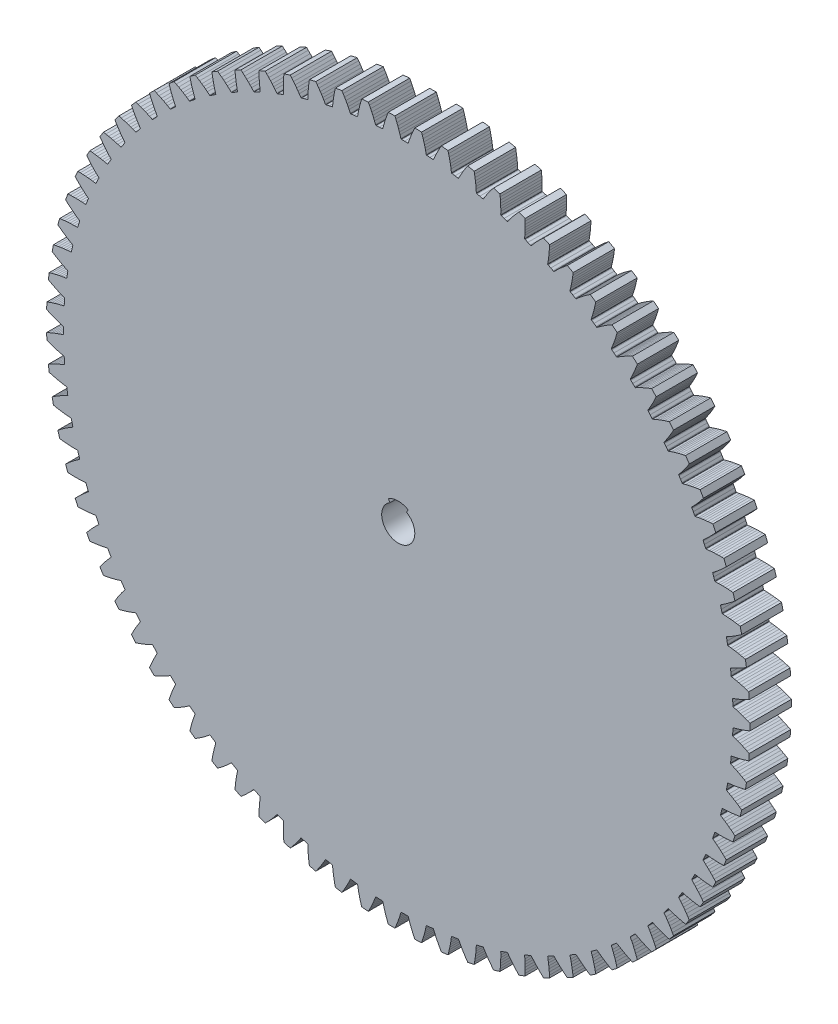
SolidWorks part; units mm, degrees
ref_plane "Front Plane" through (0, 0, 0) normal (0, 0, 1) x (1, 0, 0)
ref_plane "Top Plane" through (0, 0, 0) normal (0, 1, 0) x (1, 0, 0)
ref_plane "Right Plane" through (0, 0, 0) normal (1, 0, 0) x (0, 0, -1)
sketch "Model" plane through (0, 0, 0) normal (0, 0, 1) x (1, 0, 0)
  line L0 (4.4839, -4.2777) -> (4.7768, -4.1233)
  line L1 (4.7768, -4.1233) -> (5.0579, -3.9826)
  line L2 (5.0579, -3.9826) -> (5.326, -3.8553)
  line L3 (5.326, -3.8553) -> (5.5807, -3.7409)
  line L4 (5.5807, -3.7409) -> (5.8227, -3.6382)
  line L5 (5.8227, -3.6382) -> (6.1455, -3.5078)
  line L6 (6.1455, -3.5078) -> (6.1803, -3.4843)
  line L7 (6.1803, -3.4843) -> (6.1906, -3.4727)
  line L8 (6.1906, -3.4727) -> (6.1963, -3.4613)
  line L9 (6.1963, -3.4613) -> (6.1974, -3.4501)
  line L10 (6.1974, -3.4501) -> (6.191, -3.3763)
  line L11 (6.191, -3.3763) -> (6.1658, -3.0592)
  line L12 (6.1658, -3.0592) -> (6.1429, -2.7419)
  line L13 (6.1429, -2.7419) -> (6.1381, -2.6679)
  line L14 (6.1381, -2.6679) -> (6.1354, -2.6571)
  line L15 (6.1354, -2.6571) -> (6.128, -2.6467)
  line L16 (6.128, -2.6467) -> (6.116, -2.6367)
  line L17 (6.116, -2.6367) -> (6.0781, -2.6187)
  line L18 (6.0781, -2.6187) -> (5.7392, -2.5385)
  line L19 (5.7392, -2.5385) -> (5.4846, -2.4735)
  line L20 (5.4846, -2.4735) -> (5.2155, -2.3988)
  line L21 (5.2155, -2.3988) -> (4.9313, -2.3135)
  line L22 (4.9313, -2.3135) -> (4.6322, -2.2167)
  line L23 (4.6322, -2.2167) -> (4.3194, -2.1083)
  line L24 (4.3194, -2.1083) -> (4.0475, -2.0081)
  line L25 (4.0172, -1.2083) -> (4.2807, -1.0878)
  line L26 (4.2807, -1.0878) -> (4.5845, -0.956)
  line L27 (4.5845, -0.956) -> (4.8754, -0.8369)
  line L28 (4.8754, -0.8369) -> (5.1523, -0.7304)
  line L29 (5.1523, -0.7304) -> (5.415, -0.6355)
  line L30 (5.415, -0.6355) -> (5.664, -0.5514)
  line L31 (5.664, -0.5514) -> (5.9958, -0.4458)
  line L32 (5.9958, -0.4458) -> (6.0322, -0.425)
  line L33 (6.0322, -0.425) -> (6.0434, -0.4142)
  line L34 (6.0434, -0.4142) -> (6.05, -0.4032)
  line L35 (6.05, -0.4032) -> (6.0519, -0.3922)
  line L36 (6.0519, -0.3922) -> (6.0511, -0.3181)
  line L37 (6.0511, -0.3181) -> (6.05, 0)
  line L38 (6.05, 0) -> (6.0511, 0.3181)
  line L39 (6.0511, 0.3181) -> (6.0519, 0.3922)
  line L40 (6.0519, 0.3922) -> (6.05, 0.4032)
  line L41 (6.05, 0.4032) -> (6.0434, 0.4142)
  line L42 (6.0434, 0.4142) -> (6.0322, 0.425)
  line L43 (6.0322, 0.425) -> (5.9958, 0.4458)
  line L44 (5.9958, 0.4458) -> (5.664, 0.5514)
  line L45 (5.664, 0.5514) -> (5.415, 0.6355)
  line L46 (5.415, 0.6355) -> (5.1523, 0.7304)
  line L47 (5.1523, 0.7304) -> (4.8754, 0.8369)
  line L48 (4.8754, 0.8369) -> (4.5845, 0.956)
  line L49 (4.5845, 0.956) -> (4.2807, 1.0878)
  line L50 (4.2807, 1.0878) -> (4.0172, 1.2083)
  line L51 (4.0475, 2.0081) -> (4.3194, 2.1083)
  line L52 (4.3194, 2.1083) -> (4.6322, 2.2167)
  line L53 (4.6322, 2.2167) -> (4.9313, 2.3135)
  line L54 (4.9313, 2.3135) -> (5.2155, 2.3988)
  line L55 (5.2155, 2.3988) -> (5.4846, 2.4735)
  line L56 (5.4846, 2.4735) -> (5.7392, 2.5385)
  line L57 (5.7392, 2.5385) -> (6.0781, 2.6187)
  line L58 (6.0781, 2.6187) -> (6.116, 2.6367)
  line L59 (6.116, 2.6367) -> (6.128, 2.6467)
  line L60 (6.128, 2.6467) -> (6.1354, 2.6571)
  line L61 (6.1354, 2.6571) -> (6.1381, 2.6679)
  line L62 (6.1381, 2.6679) -> (6.1429, 2.7419)
  line L63 (6.1429, 2.7419) -> (6.1658, 3.0592)
  line L64 (6.1658, 3.0592) -> (6.191, 3.3763)
  line L65 (6.191, 3.3763) -> (6.1974, 3.4501)
  line L66 (6.1974, 3.4501) -> (6.1963, 3.4613)
  line L67 (6.1963, 3.4613) -> (6.1906, 3.4727)
  line L68 (6.1906, 3.4727) -> (6.1803, 3.4843)
  line L69 (6.1803, 3.4843) -> (6.1455, 3.5078)
  line L70 (6.1455, 3.5078) -> (5.8227, 3.6382)
  line L71 (5.8227, 3.6382) -> (5.5807, 3.7409)
  line L72 (5.5807, 3.7409) -> (5.326, 3.8553)
  line L73 (5.326, 3.8553) -> (5.0579, 3.9826)
  line L74 (5.0579, 3.9826) -> (4.7768, 4.1233)
  line L75 (4.7768, 4.1233) -> (4.4839, 4.2777)
  line L76 (4.4839, 4.2777) -> (4.2302, 4.4178)
  line L77 (4.3209, 5.213) -> (4.5996, 5.2923)
  line L78 (4.5996, 5.2923) -> (4.9197, 5.3768)
  line L79 (4.9197, 5.3768) -> (5.2253, 5.4506)
  line L80 (5.2253, 5.4506) -> (5.5151, 5.5142)
  line L81 (5.5151, 5.5142) -> (5.7891, 5.5684)
  line L82 (5.7891, 5.5684) -> (6.048, 5.6139)
  line L83 (6.048, 5.6139) -> (6.3919, 5.6683)
  line L84 (6.3919, 5.6683) -> (6.431, 5.6834)
  line L85 (6.431, 5.6834) -> (6.4438, 5.6924)
  line L86 (6.4438, 5.6924) -> (6.4519, 5.7022)
  line L87 (6.4519, 5.7022) -> (6.4554, 5.7128)
  line L88 (6.4554, 5.7128) -> (6.4658, 5.7862)
  line L89 (6.4658, 5.7862) -> (6.5127, 6.1008)
  line L90 (6.5127, 6.1008) -> (6.5618, 6.4151)
  line L91 (6.5618, 6.4151) -> (6.5738, 6.4883)
  line L92 (6.5738, 6.4883) -> (6.5735, 6.4995)
  line L93 (6.5735, 6.4995) -> (6.5687, 6.5113)
  line L94 (6.5687, 6.5113) -> (6.5592, 6.5237)
  line L95 (6.5592, 6.5237) -> (6.5264, 6.5497)
  line L96 (6.5264, 6.5497) -> (6.2143, 6.7042)
  line L97 (6.2143, 6.7042) -> (5.9808, 6.8248)
  line L98 (5.9808, 6.8248) -> (5.7355, 6.9582)
  line L99 (5.7355, 6.9582) -> (5.4778, 7.1054)
  line L100 (5.4778, 7.1054) -> (5.2081, 7.267)
  line L101 (5.2081, 7.267) -> (4.9278, 7.443)
  line L102 (4.9278, 7.443) -> (4.6854, 7.6019)
  line L103 (4.836, 8.388) -> (5.1199, 8.4461)
  line L104 (5.1199, 8.4461) -> (5.4455, 8.5061)
  line L105 (5.4455, 8.5061) -> (5.7558, 8.5566)
  line L106 (5.7558, 8.5566) -> (6.0496, 8.5981)
  line L107 (6.0496, 8.5981) -> (6.3268, 8.6314)
  line L108 (6.3268, 8.6314) -> (6.5884, 8.6572)
  line L109 (6.5884, 8.6572) -> (6.9355, 8.6854)
  line L110 (6.9355, 8.6854) -> (6.9756, 8.6975)
  line L111 (6.9756, 8.6975) -> (6.989, 8.7055)
  line L112 (6.989, 8.7055) -> (6.9979, 8.7147)
  line L113 (6.9979, 8.7147) -> (7.0022, 8.725)
  line L114 (7.0022, 8.725) -> (7.0181, 8.7974)
  line L115 (7.0181, 8.7974) -> (7.0886, 9.1076)
  line L116 (7.0886, 9.1076) -> (7.1614, 9.4172)
  line L117 (7.1614, 9.4172) -> (7.1788, 9.4893)
  line L118 (7.1788, 9.4893) -> (7.1794, 9.5004)
  line L119 (7.1794, 9.5004) -> (7.1755, 9.5126)
  line L120 (7.1755, 9.5126) -> (7.167, 9.5256)
  line L121 (7.167, 9.5256) -> (7.1362, 9.5541)
  line L122 (7.1362, 9.5541) -> (6.8367, 9.7317)
  line L123 (6.8367, 9.7317) -> (6.613, 9.8697)
  line L124 (6.613, 9.8697) -> (6.3785, 10.0213)
  line L125 (6.3785, 10.0213) -> (6.1327, 10.1875)
  line L126 (6.1327, 10.1875) -> (5.876, 10.369)
  line L127 (5.876, 10.369) -> (5.6097, 10.5658)
  line L128 (5.6097, 10.5658) -> (5.3801, 10.7425)
  line L129 (5.5897, 11.515) -> (5.8771, 11.5514)
  line L130 (5.8771, 11.5514) -> (6.2064, 11.5866)
  line L131 (6.2064, 11.5866) -> (6.5196, 11.6135)
  line L132 (6.5196, 11.6135) -> (6.8157, 11.6327)
  line L133 (6.8157, 11.6327) -> (7.0947, 11.6449)
  line L134 (7.0947, 11.6449) -> (7.3574, 11.6509)
  line L135 (7.3574, 11.6509) -> (7.7056, 11.6527)
  line L136 (7.7056, 11.6527) -> (7.7466, 11.6617)
  line L137 (7.7466, 11.6617) -> (7.7605, 11.6687)
  line L138 (7.7605, 11.6687) -> (7.7701, 11.6772)
  line L139 (7.7701, 11.6772) -> (7.7752, 11.6872)
  line L140 (7.7752, 11.6872) -> (7.7965, 11.7581)
  line L141 (7.7965, 11.7581) -> (7.8903, 12.0621)
  line L142 (7.8903, 12.0621) -> (7.9862, 12.3654)
  line L143 (7.9862, 12.3654) -> (8.0091, 12.4359)
  line L144 (8.0091, 12.4359) -> (8.0106, 12.447)
  line L145 (8.0106, 12.447) -> (8.0076, 12.4594)
  line L146 (8.0076, 12.4594) -> (8.0001, 12.4731)
  line L147 (8.0001, 12.4731) -> (7.9715, 12.5038)
  line L148 (7.9715, 12.5038) -> (7.6863, 12.7035)
  line L149 (7.6863, 12.7035) -> (7.4737, 12.8581)
  line L150 (7.4737, 12.8581) -> (7.2513, 13.0269)
  line L151 (7.2513, 13.0269) -> (7.0187, 13.2112)
  line L152 (7.0187, 13.2112) -> (6.7765, 13.4117)
  line L153 (6.7765, 13.4117) -> (6.5259, 13.628)
  line L154 (6.5259, 13.628) -> (6.3103, 13.8216)
  line L155 (6.5777, 14.576) -> (6.8671, 14.5906)
  line L156 (6.8671, 14.5906) -> (7.198, 14.6008)
  line L157 (7.198, 14.6008) -> (7.5124, 14.6039)
  line L158 (7.5124, 14.6039) -> (7.8091, 14.6006)
  line L159 (7.8091, 14.6006) -> (8.0882, 14.5917)
  line L160 (8.0882, 14.5917) -> (8.3507, 14.5778)
  line L161 (8.3507, 14.5778) -> (8.698, 14.5533)
  line L162 (8.698, 14.5533) -> (8.7396, 14.5592)
  line L163 (8.7396, 14.5592) -> (8.754, 14.5651)
  line L164 (8.754, 14.5651) -> (8.7641, 14.5729)
  line L165 (8.7641, 14.5729) -> (8.7699, 14.5824)
  line L166 (8.7699, 14.5824) -> (8.7966, 14.6516)
  line L167 (8.7966, 14.6516) -> (8.9131, 14.9476)
  line L168 (8.9131, 14.9476) -> (9.0317, 15.2427)
  line L169 (9.0317, 15.2427) -> (9.0598, 15.3113)
  line L170 (9.0598, 15.3113) -> (9.0621, 15.3223)
  line L171 (9.0621, 15.3223) -> (9.0601, 15.3349)
  line L172 (9.0601, 15.3349) -> (9.0537, 15.3491)
  line L173 (9.0537, 15.3491) -> (9.0275, 15.3819)
  line L174 (9.0275, 15.3819) -> (8.7582, 15.6026)
  line L175 (8.7582, 15.6026) -> (8.5579, 15.7727)
  line L176 (8.5579, 15.7727) -> (8.3489, 15.958)
  line L177 (8.3489, 15.958) -> (8.131, 16.1593)
  line L178 (8.131, 16.1593) -> (7.9046, 16.3775)
  line L179 (7.9046, 16.3775) -> (7.6711, 16.6122)
  line L180 (7.6711, 16.6122) -> (7.4707, 16.8215)
  line L181 (7.7944, 17.5535) -> (8.0841, 17.5462)
  line L182 (8.0841, 17.5462) -> (8.4148, 17.5313)
  line L183 (8.4148, 17.5313) -> (8.7285, 17.5107)
  line L184 (8.7285, 17.5107) -> (9.0241, 17.485)
  line L185 (9.0241, 17.485) -> (9.3018, 17.4549)
  line L186 (9.3018, 17.4549) -> (9.5624, 17.4212)
  line L187 (9.5624, 17.4212) -> (9.9069, 17.3706)
  line L188 (9.9069, 17.3706) -> (9.9488, 17.3733)
  line L189 (9.9488, 17.3733) -> (9.9636, 17.3781)
  line L190 (9.9636, 17.3781) -> (9.9743, 17.3851)
  line L191 (9.9743, 17.3851) -> (9.9808, 17.3941)
  line L192 (9.9808, 17.3941) -> (10.0127, 17.4611)
  line L193 (10.0127, 17.4611) -> (10.1512, 17.7474)
  line L194 (10.1512, 17.7474) -> (10.2918, 18.0328)
  line L195 (10.2918, 18.0328) -> (10.325, 18.099)
  line L196 (10.325, 18.099) -> (10.3282, 18.1097)
  line L197 (10.3282, 18.1097) -> (10.3271, 18.1225)
  line L198 (10.3271, 18.1225) -> (10.3217, 18.1371)
  line L199 (10.3217, 18.1371) -> (10.2981, 18.1718)
  line L200 (10.2981, 18.1718) -> (10.0463, 18.4123)
  line L201 (10.0463, 18.4123) -> (9.8594, 18.5971)
  line L202 (9.8594, 18.5971) -> (9.665, 18.7976)
  line L203 (9.665, 18.7976) -> (9.463, 19.0148)
  line L204 (9.463, 19.0148) -> (9.2537, 19.2495)
  line L205 (9.2537, 19.2495) -> (9.0386, 19.5012)
  line L206 (9.0386, 19.5012) -> (8.8547, 19.7251)
  line L207 (9.2328, 20.4305) -> (9.5211, 20.4013)
  line L208 (9.5211, 20.4013) -> (9.8498, 20.3614)
  line L209 (9.8498, 20.3614) -> (10.161, 20.3171)
  line L210 (10.161, 20.3171) -> (10.4538, 20.2691)
  line L211 (10.4538, 20.2691) -> (10.7284, 20.2182)
  line L212 (10.7284, 20.2182) -> (10.9858, 20.1649)
  line L213 (10.9858, 20.1649) -> (11.3254, 20.0883)
  line L214 (11.3254, 20.0883) -> (11.3674, 20.0879)
  line L215 (11.3674, 20.0879) -> (11.3825, 20.0915)
  line L216 (11.3825, 20.0915) -> (11.3937, 20.0977)
  line L217 (11.3937, 20.0977) -> (11.4009, 20.1062)
  line L218 (11.4009, 20.1062) -> (11.4377, 20.1705)
  line L219 (11.4377, 20.1705) -> (11.5976, 20.4456)
  line L220 (11.5976, 20.4456) -> (11.7593, 20.7195)
  line L221 (11.7593, 20.7195) -> (11.7974, 20.7831)
  line L222 (11.7974, 20.7831) -> (11.8014, 20.7935)
  line L223 (11.8014, 20.7935) -> (11.8012, 20.8063)
  line L224 (11.8012, 20.8063) -> (11.797, 20.8213)
  line L225 (11.797, 20.8213) -> (11.7761, 20.8577)
  line L226 (11.7761, 20.8577) -> (11.5432, 21.1165)
  line L227 (11.5432, 21.1165) -> (11.3708, 21.3149)
  line L228 (11.3708, 21.3149) -> (11.1921, 21.5295)
  line L229 (11.1921, 21.5295) -> (11.0071, 21.7614)
  line L230 (11.0071, 21.7614) -> (10.8162, 22.0113)
  line L231 (10.8162, 22.0113) -> (10.6208, 22.2785)
  line L232 (10.6208, 22.2785) -> (10.4543, 22.5157)
  line L233 (10.8847, 23.1905) -> (11.1699, 23.1395)
  line L234 (11.1699, 23.1395) -> (11.4947, 23.0749)
  line L235 (11.4947, 23.0749) -> (11.8017, 23.0072)
  line L236 (11.8017, 23.0072) -> (12.09, 22.9372)
  line L237 (12.09, 22.9372) -> (12.3599, 22.8657)
  line L238 (12.3599, 22.8657) -> (12.6125, 22.793)
  line L239 (12.6125, 22.793) -> (12.9454, 22.691)
  line L240 (12.9454, 22.691) -> (12.9872, 22.6874)
  line L241 (12.9872, 22.6874) -> (13.0026, 22.6899)
  line L242 (13.0026, 22.6899) -> (13.0142, 22.6951)
  line L243 (13.0142, 22.6951) -> (13.0221, 22.7031)
  line L244 (13.0221, 22.7031) -> (13.0636, 22.7645)
  line L245 (13.0636, 22.7645) -> (13.2438, 23.0267)
  line L246 (13.2438, 23.0267) -> (13.4258, 23.2876)
  line L247 (13.4258, 23.2876) -> (13.4686, 23.3481)
  line L248 (13.4686, 23.3481) -> (13.4733, 23.3582)
  line L249 (13.4733, 23.3582) -> (13.4742, 23.3709)
  line L250 (13.4742, 23.3709) -> (13.4711, 23.3862)
  line L251 (13.4711, 23.3862) -> (13.453, 23.4241)
  line L252 (13.453, 23.4241) -> (13.2403, 23.6997)
  line L253 (13.2403, 23.6997) -> (13.0835, 23.9106)
  line L254 (13.0835, 23.9106) -> (12.9215, 24.1381)
  line L255 (12.9215, 24.1381) -> (12.7545, 24.3834)
  line L256 (12.7545, 24.3834) -> (12.5831, 24.6469)
  line L257 (12.5831, 24.6469) -> (12.4084, 24.9282)
  line L258 (12.4084, 24.9282) -> (12.2603, 25.1773)
  line L259 (12.7405, 25.8176) -> (13.0211, 25.7452)
  line L260 (13.0211, 25.7452) -> (13.34, 25.6563)
  line L261 (13.34, 25.6563) -> (13.641, 25.5655)
  line L262 (13.641, 25.5655) -> (13.9232, 25.4739)
  line L263 (13.9232, 25.4739) -> (14.187, 25.3822)
  line L264 (14.187, 25.3822) -> (14.4334, 25.2906)
  line L265 (14.4334, 25.2906) -> (14.7576, 25.1637)
  line L266 (14.7576, 25.1637) -> (14.799, 25.1569)
  line L267 (14.799, 25.1569) -> (14.8146, 25.1582)
  line L268 (14.8146, 25.1582) -> (14.8266, 25.1626)
  line L269 (14.8266, 25.1626) -> (14.8349, 25.17)
  line L270 (14.8349, 25.17) -> (14.881, 25.228)
  line L271 (14.881, 25.228) -> (15.0805, 25.4758)
  line L272 (15.0805, 25.4758) -> (15.2817, 25.7222)
  line L273 (15.2817, 25.7222) -> (15.329, 25.7793)
  line L274 (15.329, 25.7793) -> (15.3345, 25.789)
  line L275 (15.3345, 25.789) -> (15.3363, 25.8017)
  line L276 (15.3363, 25.8017) -> (15.3344, 25.8172)
  line L277 (15.3344, 25.8172) -> (15.3192, 25.8563)
  line L278 (15.3192, 25.8563) -> (15.128, 26.1473)
  line L279 (15.128, 26.1473) -> (14.9875, 26.3694)
  line L280 (14.9875, 26.3694) -> (14.8432, 26.6085)
  line L281 (14.8432, 26.6085) -> (14.6953, 26.8657)
  line L282 (14.6953, 26.8657) -> (14.5443, 27.1414)
  line L283 (14.5443, 27.1414) -> (14.3913, 27.4351)
  line L284 (14.3913, 27.4351) -> (14.2625, 27.6947)
  line L285 (14.7898, 28.2968) -> (15.0641, 28.2034)
  line L286 (15.0641, 28.2034) -> (15.3754, 28.0906)
  line L287 (15.3754, 28.0906) -> (15.6686, 27.9774)
  line L288 (15.6686, 27.9774) -> (15.9431, 27.8647)
  line L289 (15.9431, 27.8647) -> (16.1992, 27.7533)
  line L290 (16.1992, 27.7533) -> (16.4379, 27.6434)
  line L291 (16.4379, 27.6434) -> (16.7516, 27.4922)
  line L292 (16.7516, 27.4922) -> (16.7924, 27.4824)
  line L293 (16.7924, 27.4824) -> (16.808, 27.4825)
  line L294 (16.808, 27.4825) -> (16.8203, 27.486)
  line L295 (16.8203, 27.486) -> (16.8292, 27.4927)
  line L296 (16.8292, 27.4927) -> (16.8795, 27.5471)
  line L297 (16.8795, 27.5471) -> (17.0972, 27.7791)
  line L298 (17.0972, 27.7791) -> (17.3165, 28.0096)
  line L299 (17.3165, 28.0096) -> (17.3679, 28.0629)
  line L300 (17.3679, 28.0629) -> (17.3741, 28.0722)
  line L301 (17.3741, 28.0722) -> (17.3769, 28.0847)
  line L302 (17.3769, 28.0847) -> (17.3761, 28.1002)
  line L303 (17.3761, 28.1002) -> (17.364, 28.1404)
  line L304 (17.364, 28.1404) -> (17.1953, 28.445)
  line L305 (17.1953, 28.445) -> (17.072, 28.6771)
  line L306 (17.072, 28.6771) -> (16.9463, 28.9265)
  line L307 (16.9463, 28.9265) -> (16.8182, 29.1941)
  line L308 (16.8182, 29.1941) -> (16.6885, 29.4805)
  line L309 (16.6885, 29.4805) -> (16.5582, 29.7849)
  line L310 (16.5582, 29.7849) -> (16.4494, 30.0534)
  line L311 (17.0206, 30.614) -> (17.2871, 30.5001)
  line L312 (17.2871, 30.5001) -> (17.589, 30.3641)
  line L313 (17.589, 30.3641) -> (17.8728, 30.229)
  line L314 (17.8728, 30.229) -> (18.138, 30.0959)
  line L315 (18.138, 30.0959) -> (18.3849, 29.9654)
  line L316 (18.3849, 29.9654) -> (18.6147, 29.8377)
  line L317 (18.6147, 29.8377) -> (18.916, 29.6633)
  line L318 (18.916, 29.6633) -> (18.9559, 29.6504)
  line L319 (18.9559, 29.6504) -> (18.9715, 29.6494)
  line L320 (18.9715, 29.6494) -> (18.984, 29.6519)
  line L321 (18.984, 29.6519) -> (18.9934, 29.6579)
  line L322 (18.9934, 29.6579) -> (19.0477, 29.7084)
  line L323 (19.0477, 29.7084) -> (19.2823, 29.9232)
  line L324 (19.2823, 29.9232) -> (19.5184, 30.1365)
  line L325 (19.5184, 30.1365) -> (19.5737, 30.1858)
  line L326 (19.5737, 30.1858) -> (19.5806, 30.1946)
  line L327 (19.5806, 30.1946) -> (19.5843, 30.2068)
  line L328 (19.5843, 30.2068) -> (19.5847, 30.2224)
  line L329 (19.5847, 30.2224) -> (19.5756, 30.2633)
  line L330 (19.5756, 30.2633) -> (19.4305, 30.5798)
  line L331 (19.4305, 30.5798) -> (19.3251, 30.8206)
  line L332 (19.3251, 30.8206) -> (19.2186, 31.0787)
  line L333 (19.2186, 31.0787) -> (19.1111, 31.3553)
  line L334 (19.1111, 31.3553) -> (19.0034, 31.6507)
  line L335 (19.0034, 31.6507) -> (18.8965, 31.964)
  line L336 (18.8965, 31.964) -> (18.8083, 32.2401)
  line L337 (19.4204, 32.7558) -> (19.6774, 32.6221)
  line L338 (19.6774, 32.6221) -> (19.9682, 32.4636)
  line L339 (19.9682, 32.4636) -> (20.241, 32.3074)
  line L340 (20.241, 32.3074) -> (20.4953, 32.1547)
  line L341 (20.4953, 32.1547) -> (20.7317, 32.0059)
  line L342 (20.7317, 32.0059) -> (20.9511, 31.8612)
  line L343 (20.9511, 31.8612) -> (21.2384, 31.6645)
  line L344 (21.2384, 31.6645) -> (21.2773, 31.6486)
  line L345 (21.2773, 31.6486) -> (21.2927, 31.6464)
  line L346 (21.2927, 31.6464) -> (21.3054, 31.648)
  line L347 (21.3054, 31.648) -> (21.3152, 31.6533)
  line L348 (21.3152, 31.6533) -> (21.3732, 31.6995)
  line L349 (21.3732, 31.6995) -> (21.6233, 31.896)
  line L350 (21.6233, 31.896) -> (21.8748, 32.0907)
  line L351 (21.8748, 32.0907) -> (21.9338, 32.1357)
  line L352 (21.9338, 32.1357) -> (21.9413, 32.144)
  line L353 (21.9413, 32.144) -> (21.9459, 32.1559)
  line L354 (21.9459, 32.1559) -> (21.9475, 32.1714)
  line L355 (21.9475, 32.1714) -> (21.9415, 32.2129)
  line L356 (21.9415, 32.2129) -> (21.8207, 32.5395)
  line L357 (21.8207, 32.5395) -> (21.7339, 32.7875)
  line L358 (21.7339, 32.7875) -> (21.6471, 33.053)
  line L359 (21.6471, 33.053) -> (21.5609, 33.3369)
  line L360 (21.5609, 33.3369) -> (21.4759, 33.6395)
  line L361 (21.4759, 33.6395) -> (21.393, 33.9601)
  line L362 (21.393, 33.9601) -> (21.3259, 34.242)
  line L363 (21.9752, 34.71) -> (22.2214, 34.5572)
  line L364 (22.2214, 34.5572) -> (22.4993, 34.3772)
  line L365 (22.4993, 34.3772) -> (22.7596, 34.2009)
  line L366 (22.7596, 34.2009) -> (23.0016, 34.0293)
  line L367 (23.0016, 34.0293) -> (23.226, 33.863)
  line L368 (23.226, 33.863) -> (23.4339, 33.7022)
  line L369 (23.4339, 33.7022) -> (23.7055, 33.4843)
  line L370 (23.7055, 33.4843) -> (23.743, 33.4655)
  line L371 (23.743, 33.4655) -> (23.7582, 33.4622)
  line L372 (23.7582, 33.4622) -> (23.771, 33.4628)
  line L373 (23.771, 33.4628) -> (23.7812, 33.4673)
  line L374 (23.7812, 33.4673) -> (23.8425, 33.509)
  line L375 (23.8425, 33.509) -> (24.1068, 33.686)
  line L376 (24.1068, 33.686) -> (24.3723, 33.8612)
  line L377 (24.3723, 33.8612) -> (24.4345, 33.9016)
  line L378 (24.4345, 33.9016) -> (24.4426, 33.9092)
  line L379 (24.4426, 33.9092) -> (24.4481, 33.9208)
  line L380 (24.4481, 33.9208) -> (24.4509, 33.9361)
  line L381 (24.4509, 33.9361) -> (24.4481, 33.978)
  line L382 (24.4481, 33.978) -> (24.3523, 34.3127)
  line L383 (24.3523, 34.3127) -> (24.2845, 34.5667)
  line L384 (24.2845, 34.5667) -> (24.2181, 34.8379)
  line L385 (24.2181, 34.8379) -> (24.1535, 35.1275)
  line L386 (24.1535, 35.1275) -> (24.0916, 35.4358)
  line L387 (24.0916, 35.4358) -> (24.0332, 35.7616)
  line L388 (24.0332, 35.7616) -> (23.9877, 36.0478)
  line L389 (24.6705, 36.4654) -> (24.9045, 36.2944)
  line L390 (24.9045, 36.2944) -> (25.168, 36.0939)
  line L391 (25.168, 36.0939) -> (25.4141, 35.8984)
  line L392 (25.4141, 35.8984) -> (25.6425, 35.709)
  line L393 (25.6425, 35.709) -> (25.8537, 35.5262)
  line L394 (25.8537, 35.5262) -> (26.0488, 35.3501)
  line L395 (26.0488, 35.3501) -> (26.3032, 35.1124)
  line L396 (26.3032, 35.1124) -> (26.3392, 35.0908)
  line L397 (26.3392, 35.0908) -> (26.3541, 35.0863)
  line L398 (26.3541, 35.0863) -> (26.3669, 35.0859)
  line L399 (26.3669, 35.0859) -> (26.3774, 35.0896)
  line L400 (26.3774, 35.0896) -> (26.4416, 35.1266)
  line L401 (26.4416, 35.1266) -> (26.7186, 35.2831)
  line L402 (26.7186, 35.2831) -> (26.9966, 35.4377)
  line L403 (26.9966, 35.4377) -> (27.0616, 35.4733)
  line L404 (27.0616, 35.4733) -> (27.0703, 35.4803)
  line L405 (27.0703, 35.4803) -> (27.0767, 35.4914)
  line L406 (27.0767, 35.4914) -> (27.0806, 35.5065)
  line L407 (27.0806, 35.5065) -> (27.081, 35.5484)
  line L408 (27.081, 35.5484) -> (27.0108, 35.8895)
  line L409 (27.0108, 35.8895) -> (26.9624, 36.1478)
  line L410 (26.9624, 36.1478) -> (26.9166, 36.4233)
  line L411 (26.9166, 36.4233) -> (26.8742, 36.7169)
  line L412 (26.8742, 36.7169) -> (26.8358, 37.029)
  line L413 (26.8358, 37.029) -> (26.8022, 37.3584)
  line L414 (26.8022, 37.3584) -> (26.7784, 37.6472)
  line L415 (27.4909, 38.0119) -> (27.7112, 37.8237)
  line L416 (27.7112, 37.8237) -> (27.9588, 37.6039)
  line L417 (27.9588, 37.6039) -> (28.1895, 37.3902)
  line L418 (28.1895, 37.3902) -> (28.4029, 37.1841)
  line L419 (28.4029, 37.1841) -> (28.5996, 36.9859)
  line L420 (28.5996, 36.9859) -> (28.7809, 36.7956)
  line L421 (28.7809, 36.7956) -> (29.0165, 36.5393)
  line L422 (29.0165, 36.5393) -> (29.0508, 36.515)
  line L423 (29.0508, 36.515) -> (29.0653, 36.5094)
  line L424 (29.0653, 36.5094) -> (29.078, 36.5081)
  line L425 (29.078, 36.5081) -> (29.0888, 36.511)
  line L426 (29.0888, 36.511) -> (29.1557, 36.543)
  line L427 (29.1557, 36.543) -> (29.4436, 36.6781)
  line L428 (29.4436, 36.6781) -> (29.7326, 36.8112)
  line L429 (29.7326, 36.8112) -> (29.8001, 36.8418)
  line L430 (29.8001, 36.8418) -> (29.8093, 36.8481)
  line L431 (29.8093, 36.8481) -> (29.8164, 36.8587)
  line L432 (29.8164, 36.8587) -> (29.8215, 36.8734)
  line L433 (29.8215, 36.8734) -> (29.825, 36.9152)
  line L434 (29.825, 36.9152) -> (29.7809, 37.2606)
  line L435 (29.7809, 37.2606) -> (29.7521, 37.5219)
  line L436 (29.7521, 37.5219) -> (29.7274, 37.8001)
  line L437 (29.7274, 37.8001) -> (29.7073, 38.0961)
  line L438 (29.7073, 38.0961) -> (29.6925, 38.4101)
  line L439 (29.6925, 38.4101) -> (29.684, 38.7411)
  line L440 (29.684, 38.7411) -> (29.6821, 39.0309)
  line L441 (30.4201, 39.3406) -> (30.6256, 39.1364)
  line L442 (30.6256, 39.1364) -> (30.8558, 38.8984)
  line L443 (30.8558, 38.8984) -> (31.0697, 38.668)
  line L444 (31.0697, 38.668) -> (31.2669, 38.4463)
  line L445 (31.2669, 38.4463) -> (31.4481, 38.2338)
  line L446 (31.4481, 38.2338) -> (31.6144, 38.0303)
  line L447 (31.6144, 38.0303) -> (31.83, 37.7569)
  line L448 (31.83, 37.7569) -> (31.8623, 37.7301)
  line L449 (31.8623, 37.7301) -> (31.8764, 37.7234)
  line L450 (31.8764, 37.7234) -> (31.889, 37.7211)
  line L451 (31.889, 37.7211) -> (31.8999, 37.7232)
  line L452 (31.8999, 37.7232) -> (31.969, 37.75)
  line L453 (31.969, 37.75) -> (32.2664, 37.863)
  line L454 (32.2664, 37.863) -> (32.5646, 37.9739)
  line L455 (32.5646, 37.9739) -> (32.6342, 37.9993)
  line L456 (32.6342, 37.9993) -> (32.6439, 38.0049)
  line L457 (32.6439, 38.0049) -> (32.6518, 38.0149)
  line L458 (32.6518, 38.0149) -> (32.658, 38.0292)
  line L459 (32.658, 38.0292) -> (32.6647, 38.0706)
  line L460 (32.6647, 38.0706) -> (32.6467, 38.4184)
  line L461 (32.6467, 38.4184) -> (32.6378, 38.681)
  line L462 (32.6378, 38.681) -> (32.6342, 38.9603)
  line L463 (32.6342, 38.9603) -> (32.6365, 39.257)
  line L464 (32.6365, 39.257) -> (32.6456, 39.5712)
  line L465 (32.6456, 39.5712) -> (32.6621, 39.9019)
  line L466 (32.6621, 39.9019) -> (32.6821, 40.191)
  line L467 (33.4414, 40.4441) -> (33.6309, 40.2248)
  line L468 (33.6309, 40.2248) -> (33.8425, 39.9702)
  line L469 (33.8425, 39.9702) -> (34.0383, 39.7242)
  line L470 (34.0383, 39.7242) -> (34.2182, 39.4882)
  line L471 (34.2182, 39.4882) -> (34.3828, 39.2627)
  line L472 (34.3828, 39.2627) -> (34.5332, 39.0471)
  line L473 (34.5332, 39.0471) -> (34.7275, 38.7582)
  line L474 (34.7275, 38.7582) -> (34.7577, 38.7291)
  line L475 (34.7577, 38.7291) -> (34.7713, 38.7213)
  line L476 (34.7713, 38.7213) -> (34.7836, 38.7181)
  line L477 (34.7836, 38.7181) -> (34.7947, 38.7194)
  line L478 (34.7947, 38.7194) -> (34.8656, 38.7409)
  line L479 (34.8656, 38.7409) -> (35.1707, 38.831)
  line L480 (35.1707, 38.831) -> (35.4764, 38.9191)
  line L481 (35.4764, 38.9191) -> (35.5478, 38.9391)
  line L482 (35.5478, 38.9391) -> (35.5578, 38.944)
  line L483 (35.5578, 38.944) -> (35.5665, 38.9533)
  line L484 (35.5665, 38.9533) -> (35.5737, 38.9671)
  line L485 (35.5737, 38.9671) -> (35.5835, 39.0079)
  line L486 (35.5835, 39.0079) -> (35.5919, 39.356)
  line L487 (35.5919, 39.356) -> (35.6029, 39.6186)
  line L488 (35.6029, 39.6186) -> (35.6204, 39.8974)
  line L489 (35.6204, 39.8974) -> (35.6452, 40.193)
  line L490 (35.6452, 40.193) -> (35.678, 40.5057)
  line L491 (35.678, 40.5057) -> (35.7194, 40.8342)
  line L492 (35.7194, 40.8342) -> (35.7613, 41.1209)
  line L493 (36.5376, 41.3159) -> (36.7099, 41.0829)
  line L494 (36.7099, 41.0829) -> (36.9016, 40.813)
  line L495 (36.9016, 40.813) -> (37.0783, 40.5529)
  line L496 (37.0783, 40.5529) -> (37.2398, 40.304)
  line L497 (37.2398, 40.304) -> (37.3869, 40.0666)
  line L498 (37.3869, 40.0666) -> (37.5206, 39.8403)
  line L499 (37.5206, 39.8403) -> (37.6925, 39.5375)
  line L500 (37.6925, 39.5375) -> (37.7204, 39.5062)
  line L501 (37.7204, 39.5062) -> (37.7333, 39.4975)
  line L502 (37.7333, 39.4975) -> (37.7454, 39.4933)
  line L503 (37.7454, 39.4933) -> (37.7565, 39.4937)
  line L504 (37.7565, 39.4937) -> (37.8289, 39.5098)
  line L505 (37.8289, 39.5098) -> (38.1399, 39.5766)
  line L506 (38.1399, 39.5766) -> (38.4514, 39.6413)
  line L507 (38.4514, 39.6413) -> (38.5241, 39.6559)
  line L508 (38.5241, 39.6559) -> (38.5344, 39.66)
  line L509 (38.5344, 39.66) -> (38.5438, 39.6687)
  line L510 (38.5438, 39.6687) -> (38.552, 39.6819)
  line L511 (38.552, 39.6819) -> (38.5649, 39.7218)
  line L512 (38.5649, 39.7218) -> (38.5996, 40.0683)
  line L513 (38.5996, 40.0683) -> (38.6304, 40.3293)
  line L514 (38.6304, 40.3293) -> (38.669, 40.6059)
  line L515 (38.669, 40.6059) -> (38.716, 40.8988)
  line L516 (38.716, 40.8988) -> (38.7724, 41.2081)
  line L517 (38.7724, 41.2081) -> (38.8385, 41.5326)
  line L518 (38.8385, 41.5326) -> (38.902, 41.8153)
  line L519 (39.6908, 41.951) -> (39.845, 41.7057)
  line L520 (39.845, 41.7057) -> (40.0157, 41.422)
  line L521 (40.0157, 41.422) -> (40.1722, 41.1493)
  line L522 (40.1722, 41.1493) -> (40.3144, 40.8889)
  line L523 (40.3144, 40.8889) -> (40.4432, 40.6411)
  line L524 (40.4432, 40.6411) -> (40.5594, 40.4053)
  line L525 (40.5594, 40.4053) -> (40.7079, 40.0904)
  line L526 (40.7079, 40.0904) -> (40.7333, 40.0571)
  line L527 (40.7333, 40.0571) -> (40.7455, 40.0474)
  line L528 (40.7455, 40.0474) -> (40.7573, 40.0423)
  line L529 (40.7573, 40.0423) -> (40.7684, 40.0419)
  line L530 (40.7684, 40.0419) -> (40.8418, 40.0524)
  line L531 (40.8418, 40.0524) -> (41.157, 40.0956)
  line L532 (41.157, 40.0956) -> (41.4724, 40.1365)
  line L533 (41.4724, 40.1365) -> (41.546, 40.1455)
  line L534 (41.546, 40.1455) -> (41.5567, 40.1488)
  line L535 (41.5567, 40.1488) -> (41.5667, 40.1568)
  line L536 (41.5667, 40.1568) -> (41.5759, 40.1693)
  line L537 (41.5759, 40.1693) -> (41.5917, 40.2082)
  line L538 (41.5917, 40.2082) -> (41.6526, 40.551)
  line L539 (41.6526, 40.551) -> (41.703, 40.809)
  line L540 (41.703, 40.809) -> (41.7624, 41.0819)
  line L541 (41.7624, 41.0819) -> (41.8314, 41.3704)
  line L542 (41.8314, 41.3704) -> (41.911, 41.6746)
  line L543 (41.911, 41.6746) -> (42.0015, 41.993)
  line L544 (42.0015, 41.993) -> (42.0862, 42.2702)
  line L545 (42.883, 42.3458) -> (43.0182, 42.0895)
  line L546 (43.0182, 42.0895) -> (43.167, 41.7938)
  line L547 (43.167, 41.7938) -> (43.3024, 41.51)
  line L548 (43.3024, 41.51) -> (43.4245, 41.2396)
  line L549 (43.4245, 41.2396) -> (43.5341, 40.9828)
  line L550 (43.5341, 40.9828) -> (43.6322, 40.7389)
  line L551 (43.6322, 40.7389) -> (43.7565, 40.4136)
  line L552 (43.7565, 40.4136) -> (43.7793, 40.3785)
  line L553 (43.7793, 40.3785) -> (43.7908, 40.3679)
  line L554 (43.7908, 40.3679) -> (43.8021, 40.3619)
  line L555 (43.8021, 40.3619) -> (43.8132, 40.3607)
  line L556 (43.8132, 40.3607) -> (43.8871, 40.3657)
  line L557 (43.8871, 40.3657) -> (44.2047, 40.3848)
  line L558 (44.2047, 40.3848) -> (44.5223, 40.4018)
  line L559 (44.5223, 40.4018) -> (44.5964, 40.4052)
  line L560 (44.5964, 40.4052) -> (44.6072, 40.4077)
  line L561 (44.6072, 40.4077) -> (44.6178, 40.4149)
  line L562 (44.6178, 40.4149) -> (44.628, 40.4267)
  line L563 (44.628, 40.4267) -> (44.6467, 40.4642)
  line L564 (44.6467, 40.4642) -> (44.7333, 40.8015)
  line L565 (44.7333, 40.8015) -> (44.8031, 41.0549)
  line L566 (44.8031, 41.0549) -> (44.8829, 41.3225)
  line L567 (44.8829, 41.3225) -> (44.9736, 41.605)
  line L568 (44.9736, 41.605) -> (45.076, 41.9023)
  line L569 (45.076, 41.9023) -> (45.1903, 42.213)
  line L570 (45.1903, 42.213) -> (45.2956, 42.4829)
  line L571 (46.0959, 42.4981) -> (46.2114, 42.2323)
  line L572 (46.2114, 42.2323) -> (46.3374, 41.9261)
  line L573 (46.3374, 41.9261) -> (46.4509, 41.633)
  line L574 (46.4509, 41.633) -> (46.5522, 41.3541)
  line L575 (46.5522, 41.3541) -> (46.6421, 41.0897)
  line L576 (46.6421, 41.0897) -> (46.7215, 40.8391)
  line L577 (46.7215, 40.8391) -> (46.8208, 40.5054)
  line L578 (46.8208, 40.5054) -> (46.8409, 40.4686)
  line L579 (46.8409, 40.4686) -> (46.8515, 40.4572)
  line L580 (46.8515, 40.4572) -> (46.8623, 40.4504)
  line L581 (46.8623, 40.4504) -> (46.8733, 40.4483)
  line L582 (46.8733, 40.4483) -> (46.9474, 40.4477)
  line L583 (46.9474, 40.4477) -> (47.2655, 40.4428)
  line L584 (47.2655, 40.4428) -> (47.5835, 40.4356)
  line L585 (47.5835, 40.4356) -> (47.6576, 40.4334)
  line L586 (47.6576, 40.4334) -> (47.6686, 40.4351)
  line L587 (47.6686, 40.4351) -> (47.6797, 40.4415)
  line L588 (47.6797, 40.4415) -> (47.6907, 40.4525)
  line L589 (47.6907, 40.4525) -> (47.7123, 40.4885)
  line L590 (47.7123, 40.4885) -> (47.8241, 40.8183)
  line L591 (47.8241, 40.8183) -> (47.9129, 41.0656)
  line L592 (47.9129, 41.0656) -> (48.0127, 41.3265)
  line L593 (48.0127, 41.3265) -> (48.1245, 41.6013)
  line L594 (48.1245, 41.6013) -> (48.2491, 41.89)
  line L595 (48.2491, 41.89) -> (48.3866, 42.1911)
  line L596 (48.3866, 42.1911) -> (48.512, 42.4523)
  line L597 (49.3111, 42.4069) -> (49.4062, 42.1332)
  line L598 (49.4062, 42.1332) -> (49.5087, 41.8184)
  line L599 (49.5087, 41.8184) -> (49.5997, 41.5174)
  line L600 (49.5997, 41.5174) -> (49.6796, 41.2317)
  line L601 (49.6796, 41.2317) -> (49.7493, 40.9613)
  line L602 (49.7493, 40.9613) -> (49.8094, 40.7054)
  line L603 (49.8094, 40.7054) -> (49.8832, 40.3651)
  line L604 (49.8832, 40.3651) -> (49.9005, 40.3269)
  line L605 (49.9005, 40.3269) -> (49.9102, 40.3147)
  line L606 (49.9102, 40.3147) -> (49.9205, 40.3071)
  line L607 (49.9205, 40.3071) -> (49.9313, 40.3042)
  line L608 (49.9313, 40.3042) -> (50.0051, 40.298)
  line L609 (50.0051, 40.298) -> (50.3219, 40.269)
  line L610 (50.3219, 40.269) -> (50.6385, 40.2379)
  line L611 (50.6385, 40.2379) -> (50.7122, 40.2301)
  line L612 (50.7122, 40.2301) -> (50.7233, 40.2309)
  line L613 (50.7233, 40.2309) -> (50.7349, 40.2364)
  line L614 (50.7349, 40.2364) -> (50.7467, 40.2466)
  line L615 (50.7467, 40.2466) -> (50.7709, 40.2809)
  line L616 (50.7709, 40.2809) -> (50.9073, 40.6012)
  line L617 (50.9073, 40.6012) -> (51.0146, 40.8412)
  line L618 (51.0146, 40.8412) -> (51.1338, 41.0937)
  line L619 (51.1338, 41.0937) -> (51.2661, 41.3593)
  line L620 (51.2661, 41.3593) -> (51.4121, 41.6377)
  line L621 (51.4121, 41.6377) -> (51.572, 41.9276)
  line L622 (51.572, 41.9276) -> (51.7169, 42.1786)
  line L623 (52.5102, 42.0729) -> (52.5843, 41.7927)
  line L624 (52.5843, 41.7927) -> (52.6627, 41.4711)
  line L625 (52.6627, 41.4711) -> (52.7307, 41.1641)
  line L626 (52.7307, 41.1641) -> (52.7888, 40.8732)
  line L627 (52.7888, 40.8732) -> (52.8378, 40.5982)
  line L628 (52.8378, 40.5982) -> (52.8785, 40.3385)
  line L629 (52.8785, 40.3385) -> (52.9263, 39.9936)
  line L630 (52.9263, 39.9936) -> (52.9406, 39.9542)
  line L631 (52.9406, 39.9542) -> (52.9494, 39.9413)
  line L632 (52.9494, 39.9413) -> (52.9591, 39.933)
  line L633 (52.9591, 39.933) -> (52.9696, 39.9293)
  line L634 (52.9696, 39.9293) -> (53.0428, 39.9175)
  line L635 (53.0428, 39.9175) -> (53.3565, 39.8647)
  line L636 (53.3565, 39.8647) -> (53.6698, 39.8096)
  line L637 (53.6698, 39.8096) -> (53.7427, 39.7963)
  line L638 (53.7427, 39.7963) -> (53.7539, 39.7963)
  line L639 (53.7539, 39.7963) -> (53.7658, 39.8009)
  line L640 (53.7658, 39.8009) -> (53.7783, 39.8101)
  line L641 (53.7783, 39.8101) -> (53.805, 39.8425)
  line L642 (53.805, 39.8425) -> (53.9653, 40.1516)
  line L643 (53.9653, 40.1516) -> (54.0904, 40.3828)
  line L644 (54.0904, 40.3828) -> (54.2284, 40.6256)
  line L645 (54.2284, 40.6256) -> (54.3804, 40.8804)
  line L646 (54.3804, 40.8804) -> (54.5471, 41.147)
  line L647 (54.5471, 41.147) -> (54.7284, 41.424)
  line L648 (54.7284, 41.424) -> (54.8919, 41.6633)
  line L649 (55.6749, 41.4978) -> (55.7276, 41.2129)
  line L650 (55.7276, 41.2129) -> (55.7815, 40.8862)
  line L651 (55.7815, 40.8862) -> (55.8261, 40.575)
  line L652 (55.8261, 40.575) -> (55.862, 40.2805)
  line L653 (55.862, 40.2805) -> (55.8901, 40.0026)
  line L654 (55.8901, 40.0026) -> (55.9109, 39.7406)
  line L655 (55.9109, 39.7406) -> (55.9325, 39.3931)
  line L656 (55.9325, 39.3931) -> (55.9439, 39.3527)
  line L657 (55.9439, 39.3527) -> (55.9516, 39.3392)
  line L658 (55.9516, 39.3392) -> (55.9607, 39.3302)
  line L659 (55.9607, 39.3302) -> (55.9709, 39.3256)
  line L660 (55.9709, 39.3256) -> (56.043, 39.3083)
  line L661 (56.043, 39.3083) -> (56.3518, 39.2319)
  line L662 (56.3518, 39.2319) -> (56.66, 39.1534)
  line L663 (56.66, 39.1534) -> (56.7317, 39.1346)
  line L664 (56.7317, 39.1346) -> (56.7428, 39.1337)
  line L665 (56.7428, 39.1337) -> (56.7551, 39.1374)
  line L666 (56.7551, 39.1374) -> (56.7683, 39.1457)
  line L667 (56.7683, 39.1457) -> (56.7974, 39.1759)
  line L668 (56.7974, 39.1759) -> (56.9806, 39.472)
  line L669 (56.9806, 39.472) -> (57.1228, 39.6931)
  line L670 (57.1228, 39.6931) -> (57.2788, 39.9247)
  line L671 (57.2788, 39.9247) -> (57.4496, 40.1673)
  line L672 (57.4496, 40.1673) -> (57.6359, 40.4205)
  line L673 (57.6359, 40.4205) -> (57.8377, 40.683)
  line L674 (57.8377, 40.683) -> (58.0188, 40.9093)
  line L675 (58.7871, 40.6851) -> (58.8181, 40.397)
  line L676 (58.8181, 40.397) -> (58.8471, 40.0672)
  line L677 (58.8471, 40.0672) -> (58.868, 39.7535)
  line L678 (58.868, 39.7535) -> (58.8816, 39.4571)
  line L679 (58.8816, 39.4571) -> (58.8885, 39.1779)
  line L680 (58.8885, 39.1779) -> (58.8895, 38.9151)
  line L681 (58.8895, 38.9151) -> (58.8848, 38.5669)
  line L682 (58.8848, 38.5669) -> (58.893, 38.5258)
  line L683 (58.893, 38.5258) -> (58.8997, 38.5117)
  line L684 (58.8997, 38.5117) -> (58.9081, 38.502)
  line L685 (58.9081, 38.502) -> (58.9179, 38.4967)
  line L686 (58.9179, 38.4967) -> (58.9885, 38.474)
  line L687 (58.9885, 38.474) -> (59.2906, 38.3745)
  line L688 (59.2906, 38.3745) -> (59.592, 38.2729)
  line L689 (59.592, 38.2729) -> (59.6621, 38.2487)
  line L690 (59.6621, 38.2487) -> (59.6731, 38.247)
  line L691 (59.6731, 38.247) -> (59.6856, 38.2498)
  line L692 (59.6856, 38.2498) -> (59.6994, 38.257)
  line L693 (59.6994, 38.257) -> (59.7307, 38.285)
  line L694 (59.7307, 38.285) -> (59.9358, 38.5663)
  line L695 (59.9358, 38.5663) -> (60.0943, 38.776)
  line L696 (60.0943, 38.776) -> (60.2673, 38.9952)
  line L697 (60.2673, 38.9952) -> (60.456, 39.2242)
  line L698 (60.456, 39.2242) -> (60.661, 39.4626)
  line L699 (60.661, 39.4626) -> (60.882, 39.709)
  line L700 (60.882, 39.709) -> (61.0797, 39.921)
  line L701 (61.8289, 39.6393) -> (61.838, 39.3497)
  line L702 (61.838, 39.3497) -> (61.8419, 39.0186)
  line L703 (61.8419, 39.0186) -> (61.8391, 38.7042)
  line L704 (61.8391, 38.7042) -> (61.8302, 38.4077)
  line L705 (61.8302, 38.4077) -> (61.816, 38.1288)
  line L706 (61.816, 38.1288) -> (61.7971, 37.8666)
  line L707 (61.7971, 37.8666) -> (61.7661, 37.5198)
  line L708 (61.7661, 37.5198) -> (61.7712, 37.4782)
  line L709 (61.7712, 37.4782) -> (61.7768, 37.4636)
  line L710 (61.7768, 37.4636) -> (61.7844, 37.4533)
  line L711 (61.7844, 37.4533) -> (61.7938, 37.4473)
  line L712 (61.7938, 37.4473) -> (61.8624, 37.4194)
  line L713 (61.8624, 37.4194) -> (62.1562, 37.2973)
  line L714 (62.1562, 37.2973) -> (62.4491, 37.1731)
  line L715 (62.4491, 37.1731) -> (62.5171, 37.1437)
  line L716 (62.5171, 37.1437) -> (62.528, 37.1412)
  line L717 (62.528, 37.1412) -> (62.5406, 37.143)
  line L718 (62.5406, 37.143) -> (62.5549, 37.1492)
  line L719 (62.5549, 37.1492) -> (62.5882, 37.1747)
  line L720 (62.5882, 37.1747) -> (62.814, 37.4398)
  line L721 (62.814, 37.4398) -> (62.9879, 37.6368)
  line L722 (62.9879, 37.6368) -> (63.1771, 37.8423)
  line L723 (63.1771, 37.8423) -> (63.3825, 38.0564)
  line L724 (63.3825, 38.0564) -> (63.6049, 38.2786)
  line L725 (63.6049, 38.2786) -> (63.844, 38.5076)
  line L726 (63.844, 38.5076) -> (64.0571, 38.704)
  line L727 (64.7828, 38.3665) -> (64.77, 38.077)
  line L728 (64.77, 38.077) -> (64.7489, 37.7466)
  line L729 (64.7489, 37.7466) -> (64.7223, 37.4333)
  line L730 (64.7223, 37.4333) -> (64.691, 37.1383)
  line L731 (64.691, 37.1383) -> (64.6558, 36.8612)
  line L732 (64.6558, 36.8612) -> (64.6171, 36.6013)
  line L733 (64.6171, 36.6013) -> (64.5599, 36.2578)
  line L734 (64.5599, 36.2578) -> (64.5619, 36.2159)
  line L735 (64.5619, 36.2159) -> (64.5664, 36.201)
  line L736 (64.5664, 36.201) -> (64.5732, 36.1901)
  line L737 (64.5732, 36.1901) -> (64.5821, 36.1834)
  line L738 (64.5821, 36.1834) -> (64.6484, 36.1504)
  line L739 (64.6484, 36.1504) -> (64.9321, 36.0064)
  line L740 (64.9321, 36.0064) -> (65.2148, 35.8605)
  line L741 (65.2148, 35.8605) -> (65.2804, 35.826)
  line L742 (65.2804, 35.826) -> (65.291, 35.8227)
  line L743 (65.291, 35.8227) -> (65.3038, 35.8235)
  line L744 (65.3038, 35.8235) -> (65.3185, 35.8286)
  line L745 (65.3185, 35.8286) -> (65.3536, 35.8515)
  line L746 (65.3536, 35.8515) -> (65.5988, 36.0987)
  line L747 (65.5988, 36.0987) -> (65.7871, 36.2821)
  line L748 (65.7871, 36.2821) -> (65.9913, 36.4727)
  line L749 (65.9913, 36.4727) -> (66.2123, 36.6706)
  line L750 (66.2123, 36.6706) -> (66.4509, 36.8753)
  line L751 (66.4509, 36.8753) -> (66.7066, 37.0856)
  line L752 (66.7066, 37.0856) -> (66.934, 37.2653)
  line L753 (67.6321, 36.8739) -> (67.5974, 36.5862)
  line L754 (67.5974, 36.5862) -> (67.5514, 36.2583)
  line L755 (67.5514, 36.2583) -> (67.5012, 35.948)
  line L756 (67.5012, 35.948) -> (67.4476, 35.6562)
  line L757 (67.4476, 35.6562) -> (67.3915, 35.3826)
  line L758 (67.3915, 35.3826) -> (67.3334, 35.1263)
  line L759 (67.3334, 35.1263) -> (67.2503, 34.7881)
  line L760 (67.2503, 34.7881) -> (67.2491, 34.7462)
  line L761 (67.2491, 34.7462) -> (67.2525, 34.731)
  line L762 (67.2525, 34.731) -> (67.2584, 34.7196)
  line L763 (67.2584, 34.7196) -> (67.2668, 34.7123)
  line L764 (67.2668, 34.7123) -> (67.3305, 34.6743)
  line L765 (67.3305, 34.6743) -> (67.6024, 34.5093)
  line L766 (67.6024, 34.5093) -> (67.8732, 34.3424)
  line L767 (67.8732, 34.3424) -> (67.9361, 34.303)
  line L768 (67.9361, 34.303) -> (67.9464, 34.2989)
  line L769 (67.9464, 34.2989) -> (67.9592, 34.2988)
  line L770 (67.9592, 34.2988) -> (67.9743, 34.3027)
  line L771 (67.9743, 34.3027) -> (68.011, 34.3229)
  line L772 (68.011, 34.3229) -> (68.2742, 34.5509)
  line L773 (68.2742, 34.5509) -> (68.4759, 34.7195)
  line L774 (68.4759, 34.7195) -> (68.6938, 34.8941)
  line L775 (68.6938, 34.8941) -> (68.9292, 35.0747)
  line L776 (68.9292, 35.0747) -> (69.1826, 35.2608)
  line L777 (69.1826, 35.2608) -> (69.4535, 35.4512)
  line L778 (69.4535, 35.4512) -> (69.6938, 35.6132)
  line L779 (70.3603, 35.1701) -> (70.3039, 34.8859)
  line L780 (70.3039, 34.8859) -> (70.2333, 34.5624)
  line L781 (70.2333, 34.5624) -> (70.1597, 34.2567)
  line L782 (70.1597, 34.2567) -> (70.0843, 33.9698)
  line L783 (70.0843, 33.9698) -> (70.0076, 33.7012)
  line L784 (70.0076, 33.7012) -> (69.9302, 33.4501)
  line L785 (69.9302, 33.4501) -> (69.8219, 33.1192)
  line L786 (69.8219, 33.1192) -> (69.8175, 33.0774)
  line L787 (69.8175, 33.0774) -> (69.8197, 33.062)
  line L788 (69.8197, 33.062) -> (69.8248, 33.0503)
  line L789 (69.8248, 33.0503) -> (69.8326, 33.0423)
  line L790 (69.8326, 33.0423) -> (69.8932, 32.9996)
  line L791 (69.8932, 32.9996) -> (70.1519, 32.8145)
  line L792 (70.1519, 32.8145) -> (70.4093, 32.6276)
  line L793 (70.4093, 32.6276) -> (70.469, 32.5836)
  line L794 (70.469, 32.5836) -> (70.479, 32.5787)
  line L795 (70.479, 32.5787) -> (70.4917, 32.5776)
  line L796 (70.4917, 32.5776) -> (70.5071, 32.5804)
  line L797 (70.5071, 32.5804) -> (70.5452, 32.5978)
  line L798 (70.5452, 32.5978) -> (70.8249, 32.8052)
  line L799 (70.8249, 32.8052) -> (71.0387, 32.9581)
  line L800 (71.0387, 32.9581) -> (71.2693, 33.1157)
  line L801 (71.2693, 33.1157) -> (71.5176, 33.278)
  line L802 (71.5176, 33.278) -> (71.7844, 33.4444)
  line L803 (71.7844, 33.4444) -> (72.0689, 33.6137)
  line L804 (72.0689, 33.6137) -> (72.3207, 33.7571)
  line L805 (72.9518, 33.2649) -> (72.8741, 32.9857)
  line L806 (72.8741, 32.9857) -> (72.7792, 32.6685)
  line L807 (72.7792, 32.6685) -> (72.6828, 32.3693)
  line L808 (72.6828, 32.3693) -> (72.5858, 32.0889)
  line L809 (72.5858, 32.0889) -> (72.4891, 31.8269)
  line L810 (72.4891, 31.8269) -> (72.3929, 31.5823)
  line L811 (72.3929, 31.5823) -> (72.2599, 31.2605)
  line L812 (72.2599, 31.2605) -> (72.2523, 31.2192)
  line L813 (72.2523, 31.2192) -> (72.2534, 31.2037)
  line L814 (72.2534, 31.2037) -> (72.2575, 31.1916)
  line L815 (72.2575, 31.1916) -> (72.2647, 31.1831)
  line L816 (72.2647, 31.1831) -> (72.3219, 31.1359)
  line L817 (72.3219, 31.1359) -> (72.5659, 30.9318)
  line L818 (72.5659, 30.9318) -> (72.8084, 30.7259)
  line L819 (72.8084, 30.7259) -> (72.8646, 30.6776)
  line L820 (72.8646, 30.6776) -> (72.8742, 30.6719)
  line L821 (72.8742, 30.6719) -> (72.8868, 30.6699)
  line L822 (72.8868, 30.6699) -> (72.9023, 30.6715)
  line L823 (72.9023, 30.6715) -> (72.9417, 30.6859)
  line L824 (72.9417, 30.6859) -> (73.2363, 30.8716)
  line L825 (73.2363, 30.8716) -> (73.461, 31.0078)
  line L826 (73.461, 31.0078) -> (73.7028, 31.1476)
  line L827 (73.7028, 31.1476) -> (73.9628, 31.2906)
  line L828 (73.9628, 31.2906) -> (74.2413, 31.4364)
  line L829 (74.2413, 31.4364) -> (74.5378, 31.5837)
  line L830 (74.5378, 31.5837) -> (74.7998, 31.7076)
  line L831 (75.3919, 31.1691) -> (75.2933, 30.8966)
  line L832 (75.2933, 30.8966) -> (75.1746, 30.5875)
  line L833 (75.1746, 30.5875) -> (75.0558, 30.2964)
  line L834 (75.0558, 30.2964) -> (74.938, 30.0241)
  line L835 (74.938, 30.0241) -> (74.8217, 29.7702)
  line L836 (74.8217, 29.7702) -> (74.7073, 29.5336)
  line L837 (74.7073, 29.5336) -> (74.5503, 29.2228)
  line L838 (74.5503, 29.2228) -> (74.5396, 29.1822)
  line L839 (74.5396, 29.1822) -> (74.5395, 29.1666)
  line L840 (74.5395, 29.1666) -> (74.5427, 29.1543)
  line L841 (74.5427, 29.1543) -> (74.5493, 29.1452)
  line L842 (74.5493, 29.1452) -> (74.6027, 29.0938)
  line L843 (74.6027, 29.0938) -> (74.8305, 28.8718)
  line L844 (74.8305, 28.8718) -> (75.0568, 28.6482)
  line L845 (75.0568, 28.6482) -> (75.1092, 28.5958)
  line L846 (75.1092, 28.5958) -> (75.1184, 28.5894)
  line L847 (75.1184, 28.5894) -> (75.1308, 28.5864)
  line L848 (75.1308, 28.5864) -> (75.1463, 28.5869)
  line L849 (75.1463, 28.5869) -> (75.1867, 28.5983)
  line L850 (75.1867, 28.5983) -> (75.4945, 28.7611)
  line L851 (75.4945, 28.7611) -> (75.7289, 28.88)
  line L852 (75.7289, 28.88) -> (75.9806, 29.001)
  line L853 (75.9806, 29.001) -> (76.2506, 29.124)
  line L854 (76.2506, 29.124) -> (76.5394, 29.2483)
  line L855 (76.5394, 29.2483) -> (76.8461, 29.3728)
  line L856 (76.8461, 29.3728) -> (77.1167, 29.4765)
  line L857 (77.6664, 28.8947) -> (77.5475, 28.6305)
  line L858 (77.5475, 28.6305) -> (77.4058, 28.3313)
  line L859 (77.4058, 28.3313) -> (77.2653, 28.05)
  line L860 (77.2653, 28.05) -> (77.1272, 27.7874)
  line L861 (77.1272, 27.7874) -> (76.9921, 27.543)
  line L862 (76.9921, 27.543) -> (76.8601, 27.3157)
  line L863 (76.8601, 27.3157) -> (76.68, 27.0177)
  line L864 (76.68, 27.0177) -> (76.6663, 26.978)
  line L865 (76.6663, 26.978) -> (76.665, 26.9625)
  line L866 (76.665, 26.9625) -> (76.6673, 26.9499)
  line L867 (76.6673, 26.9499) -> (76.6731, 26.9404)
  line L868 (76.6731, 26.9404) -> (76.7226, 26.8852)
  line L869 (76.7226, 26.8852) -> (76.9329, 26.6465)
  line L870 (76.9329, 26.6465) -> (77.1417, 26.4065)
  line L871 (77.1417, 26.4065) -> (77.1899, 26.3502)
  line L872 (77.1899, 26.3502) -> (77.1986, 26.3432)
  line L873 (77.1986, 26.3432) -> (77.2107, 26.3393)
  line L874 (77.2107, 26.3393) -> (77.2263, 26.3385)
  line L875 (77.2263, 26.3385) -> (77.2674, 26.3468)
  line L876 (77.2674, 26.3468) -> (77.5866, 26.486)
  line L877 (77.5866, 26.486) -> (77.8293, 26.5867)
  line L878 (77.8293, 26.5867) -> (78.0895, 26.6884)
  line L879 (78.0895, 26.6884) -> (78.368, 26.7906)
  line L880 (78.368, 26.7906) -> (78.6653, 26.8927)
  line L881 (78.6653, 26.8927) -> (78.9807, 26.9936)
  line L882 (78.9807, 26.9936) -> (79.2583, 27.0766)
  line L883 (79.7624, 26.4549) -> (79.6239, 26.2004)
  line L884 (79.6239, 26.2004) -> (79.4599, 25.9127)
  line L885 (79.4599, 25.9127) -> (79.2986, 25.6429)
  line L886 (79.2986, 25.6429) -> (79.141, 25.3915)
  line L887 (79.141, 25.3915) -> (78.9878, 25.158)
  line L888 (78.9878, 25.158) -> (78.839, 24.9414)
  line L889 (78.839, 24.9414) -> (78.6369, 24.6578)
  line L890 (78.6369, 24.6578) -> (78.6203, 24.6193)
  line L891 (78.6203, 24.6193) -> (78.6178, 24.6039)
  line L892 (78.6178, 24.6039) -> (78.6191, 24.5912)
  line L893 (78.6191, 24.5912) -> (78.6242, 24.5813)
  line L894 (78.6242, 24.5813) -> (78.6693, 24.5225)
  line L895 (78.6693, 24.5225) -> (78.861, 24.2686)
  line L896 (78.861, 24.2686) -> (79.051, 24.0135)
  line L897 (79.051, 24.0135) -> (79.0948, 23.9537)
  line L898 (79.0948, 23.9537) -> (79.103, 23.946)
  line L899 (79.103, 23.946) -> (79.1148, 23.9412)
  line L900 (79.1148, 23.9412) -> (79.1302, 23.9393)
  line L901 (79.1302, 23.9393) -> (79.1719, 23.9445)
  line L902 (79.1719, 23.9445) -> (79.5007, 24.0591)
  line L903 (79.5007, 24.0591) -> (79.7503, 24.1412)
  line L904 (79.7503, 24.1412) -> (80.0174, 24.2229)
  line L905 (80.0174, 24.2229) -> (80.3029, 24.3038)
  line L906 (80.3029, 24.3038) -> (80.6071, 24.3831)
  line L907 (80.6071, 24.3831) -> (80.9291, 24.4599)
  line L908 (80.9291, 24.4599) -> (81.2123, 24.5216)
  line L909 (81.6679, 23.8636) -> (81.5105, 23.6203)
  line L910 (81.5105, 23.6203) -> (81.3253, 23.3458)
  line L911 (81.3253, 23.3458) -> (81.144, 23.089)
  line L912 (81.144, 23.089) -> (80.9679, 22.8502)
  line L913 (80.9679, 22.8502) -> (80.7974, 22.629)
  line L914 (80.7974, 22.629) -> (80.6327, 22.4242)
  line L915 (80.6327, 22.4242) -> (80.4097, 22.1567)
  line L916 (80.4097, 22.1567) -> (80.3902, 22.1196)
  line L917 (80.3902, 22.1196) -> (80.3866, 22.1044)
  line L918 (80.3866, 22.1044) -> (80.3869, 22.0917)
  line L919 (80.3869, 22.0917) -> (80.3912, 22.0814)
  line L920 (80.3912, 22.0814) -> (80.4318, 22.0193)
  line L921 (80.4318, 22.0193) -> (80.6038, 21.7517)
  line L922 (80.6038, 21.7517) -> (80.7739, 21.4829)
  line L923 (80.7739, 21.4829) -> (80.8131, 21.42)
  line L924 (80.8131, 21.42) -> (80.8206, 21.4117)
  line L925 (80.8206, 21.4117) -> (80.832, 21.406)
  line L926 (80.832, 21.406) -> (80.8473, 21.4029)
  line L927 (80.8473, 21.4029) -> (80.8892, 21.405)
  line L928 (80.8892, 21.405) -> (81.2257, 21.4944)
  line L929 (81.2257, 21.4944) -> (81.4809, 21.5574)
  line L930 (81.4809, 21.5574) -> (81.7534, 21.6187)
  line L931 (81.7534, 21.6187) -> (82.0441, 21.6777)
  line L932 (82.0441, 21.6777) -> (82.3535, 21.7338)
  line L933 (82.3535, 21.7338) -> (82.6804, 21.786)
  line L934 (82.6804, 21.786) -> (82.9674, 21.8261)
  line L935 (83.3719, 21.1355) -> (83.1966, 20.9048)
  line L936 (83.1966, 20.9048) -> (82.9912, 20.6452)
  line L937 (82.9912, 20.6452) -> (82.791, 20.4027)
  line L938 (82.791, 20.4027) -> (82.5973, 20.178)
  line L939 (82.5973, 20.178) -> (82.4106, 19.9703)
  line L940 (82.4106, 19.9703) -> (82.2308, 19.7785)
  line L941 (82.2308, 19.7785) -> (81.9883, 19.5287)
  line L942 (81.9883, 19.5287) -> (81.966, 19.4932)
  line L943 (81.966, 19.4932) -> (81.9612, 19.4783)
  line L944 (81.9612, 19.4783) -> (81.9606, 19.4656)
  line L945 (81.9606, 19.4656) -> (81.9642, 19.455)
  line L946 (81.9642, 19.455) -> (81.9999, 19.39)
  line L947 (81.9999, 19.39) -> (82.1511, 19.1102)
  line L948 (82.1511, 19.1102) -> (82.3004, 18.8293)
  line L949 (82.3004, 18.8293) -> (82.3348, 18.7636)
  line L950 (82.3348, 18.7636) -> (82.3416, 18.7548)
  line L951 (82.3416, 18.7548) -> (82.3526, 18.7482)
  line L952 (82.3526, 18.7482) -> (82.3676, 18.744)
  line L953 (82.3676, 18.744) -> (82.4095, 18.7428)
  line L954 (82.4095, 18.7428) -> (82.7519, 18.8065)
  line L955 (82.7519, 18.8065) -> (83.0111, 18.8501)
  line L956 (83.0111, 18.8501) -> (83.2874, 18.8906)
  line L957 (83.2874, 18.8906) -> (83.5818, 18.9275)
  line L958 (83.5818, 18.9275) -> (83.8945, 18.96)
  line L959 (83.8945, 18.96) -> (84.2244, 18.9873)
  line L960 (84.2244, 18.9873) -> (84.5136, 19.0056)
  line L961 (84.8648, 18.2864) -> (84.6725, 18.0696)
  line L962 (84.6725, 18.0696) -> (84.448, 17.8263)
  line L963 (84.448, 17.8263) -> (84.2301, 17.5997)
  line L964 (84.2301, 17.5997) -> (84.0199, 17.3902)
  line L965 (84.0199, 17.3902) -> (83.8181, 17.1972)
  line L966 (83.8181, 17.1972) -> (83.6243, 17.0196)
  line L967 (83.6243, 17.0196) -> (83.3636, 16.7889)
  line L968 (83.3636, 16.7889) -> (83.3387, 16.7551)
  line L969 (83.3387, 16.7551) -> (83.3328, 16.7407)
  line L970 (83.3328, 16.7407) -> (83.3312, 16.728)
  line L971 (83.3312, 16.728) -> (83.334, 16.7172)
  line L972 (83.334, 16.7172) -> (83.3646, 16.6497)
  line L973 (83.3646, 16.6497) -> (83.4943, 16.3592)
  line L974 (83.4943, 16.3592) -> (83.6219, 16.0678)
  line L975 (83.6219, 16.0678) -> (83.6512, 15.9997)
  line L976 (83.6512, 15.9997) -> (83.6574, 15.9904)
  line L977 (83.6574, 15.9904) -> (83.6678, 15.983)
  line L978 (83.6678, 15.983) -> (83.6825, 15.9777)
  line L979 (83.6825, 15.9777) -> (83.7242, 15.9734)
  line L980 (83.7242, 15.9734) -> (84.0703, 16.011)
  line L981 (84.0703, 16.011) -> (84.3321, 16.0348)
  line L982 (84.3321, 16.0348) -> (84.6107, 16.0543)
  line L983 (84.6107, 16.0543) -> (84.907, 16.0688)
  line L984 (84.907, 16.0688) -> (85.2213, 16.0776)
  line L985 (85.2213, 16.0776) -> (85.5524, 16.0799)
  line L986 (85.5524, 16.0799) -> (85.8421, 16.0763)
  line L987 (86.1379, 15.3325) -> (85.9298, 15.1309)
  line L988 (85.9298, 15.1309) -> (85.6875, 14.9052)
  line L989 (85.6875, 14.9052) -> (85.453, 14.6958)
  line L990 (85.453, 14.6958) -> (85.2277, 14.5028)
  line L991 (85.2277, 14.5028) -> (85.0118, 14.3257)
  line L992 (85.0118, 14.3257) -> (84.8052, 14.1632)
  line L993 (84.8052, 14.1632) -> (84.5277, 13.9528)
  line L994 (84.5277, 13.9528) -> (84.5004, 13.921)
  line L995 (84.5004, 13.921) -> (84.4934, 13.9071)
  line L996 (84.4934, 13.9071) -> (84.4909, 13.8946)
  line L997 (84.4909, 13.8946) -> (84.4928, 13.8836)
  line L998 (84.4928, 13.8836) -> (84.5183, 13.814)
  line L999 (84.5183, 13.814) -> (84.6256, 13.5145)
  line L1000 (84.6256, 13.5145) -> (84.7308, 13.2143)
  line L1001 (84.7308, 13.2143) -> (84.7549, 13.1442)
  line L1002 (84.7549, 13.1442) -> (84.7603, 13.1345)
  line L1003 (84.7603, 13.1345) -> (84.7702, 13.1263)
  line L1004 (84.7702, 13.1263) -> (84.7843, 13.1199)
  line L1005 (84.7843, 13.1199) -> (84.8256, 13.1124)
  line L1006 (84.8256, 13.1124) -> (85.1736, 13.1237)
  line L1007 (85.1736, 13.1237) -> (85.4364, 13.1277)
  line L1008 (85.4364, 13.1277) -> (85.7157, 13.126)
  line L1009 (85.7157, 13.126) -> (86.0123, 13.1181)
  line L1010 (86.0123, 13.1181) -> (86.3263, 13.1031)
  line L1011 (86.3263, 13.1031) -> (86.6566, 13.0803)
  line L1012 (86.6566, 13.0803) -> (86.9453, 13.0548)
  line L1013 (87.184, 12.2909) -> (86.9612, 12.1056)
  line L1014 (86.9612, 12.1056) -> (86.7025, 11.8989)
  line L1015 (86.7025, 11.8989) -> (86.4529, 11.7077)
  line L1016 (86.4529, 11.7077) -> (86.2136, 11.5324)
  line L1017 (86.2136, 11.5324) -> (85.9849, 11.372)
  line L1018 (85.9849, 11.372) -> (85.7666, 11.2257)
  line L1019 (85.7666, 11.2257) -> (85.474, 11.0369)
  line L1020 (85.474, 11.0369) -> (85.4444, 11.0072)
  line L1021 (85.4444, 11.0072) -> (85.4364, 10.9939)
  line L1022 (85.4364, 10.9939) -> (85.4329, 10.9816)
  line L1023 (85.4329, 10.9816) -> (85.4339, 10.9705)
  line L1024 (85.4339, 10.9705) -> (85.4541, 10.8991)
  line L1025 (85.4541, 10.8991) -> (85.5385, 10.5924)
  line L1026 (85.5385, 10.5924) -> (85.6207, 10.2851)
  line L1027 (85.6207, 10.2851) -> (85.6394, 10.2134)
  line L1028 (85.6394, 10.2134) -> (85.6441, 10.2033)
  line L1029 (85.6441, 10.2033) -> (85.6533, 10.1944)
  line L1030 (85.6533, 10.1944) -> (85.6669, 10.1869)
  line L1031 (85.6669, 10.1869) -> (85.7075, 10.1763)
  line L1032 (85.7075, 10.1763) -> (86.0554, 10.1613)
  line L1033 (86.0554, 10.1613) -> (86.3178, 10.1454)
  line L1034 (86.3178, 10.1454) -> (86.5961, 10.1226)
  line L1035 (86.5961, 10.1226) -> (86.8912, 10.0923)
  line L1036 (86.8912, 10.0923) -> (87.2032, 10.0535)
  line L1037 (87.2032, 10.0535) -> (87.5309, 10.0059)
  line L1038 (87.5309, 10.0059) -> (87.8168, 9.9586)
  line L1039 (87.997, 9.1788) -> (87.7608, 9.0109)
  line L1040 (87.7608, 9.0109) -> (87.4873, 8.8243)
  line L1041 (87.4873, 8.8243) -> (87.2239, 8.6526)
  line L1042 (87.2239, 8.6526) -> (86.972, 8.4958)
  line L1043 (86.972, 8.4958) -> (86.7319, 8.3533)
  line L1044 (86.7319, 8.3533) -> (86.5031, 8.2238)
  line L1045 (86.5031, 8.2238) -> (86.1971, 8.0577)
  line L1046 (86.1971, 8.0577) -> (86.1653, 8.0304)
  line L1047 (86.1653, 8.0304) -> (86.1563, 8.0177)
  line L1048 (86.1563, 8.0177) -> (86.1519, 8.0057)
  line L1049 (86.1519, 8.0057) -> (86.1521, 7.9945)
  line L1050 (86.1521, 7.9945) -> (86.1668, 7.9219)
  line L1051 (86.1668, 7.9219) -> (86.2278, 7.6097)
  line L1052 (86.2278, 7.6097) -> (86.2865, 7.297)
  line L1053 (86.2865, 7.297) -> (86.2997, 7.2241)
  line L1054 (86.2997, 7.2241) -> (86.3036, 7.2136)
  line L1055 (86.3036, 7.2136) -> (86.3121, 7.2041)
  line L1056 (86.3121, 7.2041) -> (86.3252, 7.1956)
  line L1057 (86.3252, 7.1956) -> (86.3649, 7.182)
  line L1058 (86.3649, 7.182) -> (86.7106, 7.1407)
  line L1059 (86.7106, 7.1407) -> (86.971, 7.105)
  line L1060 (86.971, 7.105) -> (87.2468, 7.0612)
  line L1061 (87.2468, 7.0612) -> (87.5388, 7.0086)
  line L1062 (87.5388, 7.0086) -> (87.847, 6.9464)
  line L1063 (87.847, 6.9464) -> (88.1701, 6.8741)
  line L1064 (88.1701, 6.8741) -> (88.4516, 6.8054)
  line L1065 (88.5723, 6.0141) -> (88.3241, 5.8646)
  line L1066 (88.3241, 5.8646) -> (88.0373, 5.6992)
  line L1067 (88.0373, 5.6992) -> (87.7617, 5.5479)
  line L1068 (87.7617, 5.5479) -> (87.4987, 5.4107)
  line L1069 (87.4987, 5.4107) -> (87.2484, 5.2867)
  line L1070 (87.2484, 5.2867) -> (87.0105, 5.1749)
  line L1071 (87.0105, 5.1749) -> (86.6928, 5.0324)
  line L1072 (86.6928, 5.0324) -> (86.659, 5.0076)
  line L1073 (86.659, 5.0076) -> (86.6491, 4.9956)
  line L1074 (86.6491, 4.9956) -> (86.6438, 4.9839)
  line L1075 (86.6438, 4.9839) -> (86.6432, 4.9728)
  line L1076 (86.6432, 4.9728) -> (86.6524, 4.8992)
  line L1077 (86.6524, 4.8992) -> (86.6895, 4.5833)
  line L1078 (86.6895, 4.5833) -> (86.7244, 4.2671)
  line L1079 (86.7244, 4.2671) -> (86.7321, 4.1934)
  line L1080 (86.7321, 4.1934) -> (86.7352, 4.1827)
  line L1081 (86.7352, 4.1827) -> (86.7429, 4.1725)
  line L1082 (86.7429, 4.1725) -> (86.7553, 4.163)
  line L1083 (86.7553, 4.163) -> (86.7939, 4.1465)
  line L1084 (86.7939, 4.1465) -> (87.1355, 4.0792)
  line L1085 (87.1355, 4.0792) -> (87.3924, 4.0238)
  line L1086 (87.3924, 4.0238) -> (87.6642, 3.9594)
  line L1087 (87.6642, 3.9594) -> (87.9513, 3.8848)
  line L1088 (87.9513, 3.8848) -> (88.2539, 3.7995)
  line L1089 (88.2539, 3.7995) -> (88.5706, 3.703)
  line L1090 (88.5706, 3.703) -> (88.8461, 3.6131)
  line L1091 (88.9067, 2.815) -> (88.6479, 2.6847)
  line L1092 (88.6479, 2.6847) -> (88.3494, 2.5415)
  line L1093 (88.3494, 2.5415) -> (88.0631, 2.4115)
  line L1094 (88.0631, 2.4115) -> (87.7904, 2.2945)
  line L1095 (87.7904, 2.2945) -> (87.5315, 2.1898)
  line L1096 (87.5315, 2.1898) -> (87.2859, 2.0963)
  line L1097 (87.2859, 2.0963) -> (86.9583, 1.9782)
  line L1098 (86.9583, 1.9782) -> (86.9227, 1.9561)
  line L1099 (86.9227, 1.9561) -> (86.9119, 1.9448)
  line L1100 (86.9119, 1.9448) -> (86.9058, 1.9336)
  line L1101 (86.9058, 1.9336) -> (86.9043, 1.9226)
  line L1102 (86.9043, 1.9226) -> (86.9079, 1.8485)
  line L1103 (86.9079, 1.8485) -> (86.921, 1.5307)
  line L1104 (86.921, 1.5307) -> (86.932, 1.2128)
  line L1105 (86.932, 1.2128) -> (86.934, 1.1387)
  line L1106 (86.934, 1.1387) -> (86.9363, 1.1277)
  line L1107 (86.9363, 1.1277) -> (86.9433, 1.117)
  line L1108 (86.9433, 1.117) -> (86.9549, 1.1067)
  line L1109 (86.9549, 1.1067) -> (86.9921, 1.0872)
  line L1110 (86.9921, 1.0872) -> (87.3276, 0.9943)
  line L1111 (87.3276, 0.9943) -> (87.5796, 0.9197)
  line L1112 (87.5796, 0.9197) -> (87.8457, 0.8348)
  line L1113 (87.8457, 0.8348) -> (88.1264, 0.7388)
  line L1114 (88.1264, 0.7388) -> (88.4217, 0.6308)
  line L1115 (88.4217, 0.6308) -> (88.7302, 0.5106)
  line L1116 (88.7302, 0.5106) -> (88.9981, 0.4002)
  line L1117 (88.9981, -0.4002) -> (88.7302, -0.5106)
  line L1118 (88.7302, -0.5106) -> (88.4217, -0.6308)
  line L1119 (88.4217, -0.6308) -> (88.1264, -0.7388)
  line L1120 (88.1264, -0.7388) -> (87.8457, -0.8348)
  line L1121 (87.8457, -0.8348) -> (87.5796, -0.9197)
  line L1122 (87.5796, -0.9197) -> (87.3276, -0.9943)
  line L1123 (87.3276, -0.9943) -> (86.9921, -1.0872)
  line L1124 (86.9921, -1.0872) -> (86.9549, -1.1067)
  line L1125 (86.9549, -1.1067) -> (86.9433, -1.117)
  line L1126 (86.9433, -1.117) -> (86.9363, -1.1277)
  line L1127 (86.9363, -1.1277) -> (86.934, -1.1387)
  line L1128 (86.934, -1.1387) -> (86.932, -1.2128)
  line L1129 (86.932, -1.2128) -> (86.921, -1.5307)
  line L1130 (86.921, -1.5307) -> (86.9079, -1.8485)
  line L1131 (86.9079, -1.8485) -> (86.9043, -1.9226)
  line L1132 (86.9043, -1.9226) -> (86.9058, -1.9336)
  line L1133 (86.9058, -1.9336) -> (86.9119, -1.9448)
  line L1134 (86.9119, -1.9448) -> (86.9227, -1.9561)
  line L1135 (86.9227, -1.9561) -> (86.9583, -1.9782)
  line L1136 (86.9583, -1.9782) -> (87.2859, -2.0963)
  line L1137 (87.2859, -2.0963) -> (87.5315, -2.1898)
  line L1138 (87.5315, -2.1898) -> (87.7904, -2.2945)
  line L1139 (87.7904, -2.2945) -> (88.0631, -2.4115)
  line L1140 (88.0631, -2.4115) -> (88.3494, -2.5415)
  line L1141 (88.3494, -2.5415) -> (88.6479, -2.6847)
  line L1142 (88.6479, -2.6847) -> (88.9067, -2.815)
  line L1143 (88.8461, -3.6131) -> (88.5706, -3.703)
  line L1144 (88.5706, -3.703) -> (88.2539, -3.7995)
  line L1145 (88.2539, -3.7995) -> (87.9513, -3.8848)
  line L1146 (87.9513, -3.8848) -> (87.6642, -3.9594)
  line L1147 (87.6642, -3.9594) -> (87.3924, -4.0238)
  line L1148 (87.3924, -4.0238) -> (87.1355, -4.0792)
  line L1149 (87.1355, -4.0792) -> (86.7939, -4.1465)
  line L1150 (86.7939, -4.1465) -> (86.7553, -4.163)
  line L1151 (86.7553, -4.163) -> (86.7429, -4.1725)
  line L1152 (86.7429, -4.1725) -> (86.7352, -4.1827)
  line L1153 (86.7352, -4.1827) -> (86.7321, -4.1934)
  line L1154 (86.7321, -4.1934) -> (86.7244, -4.2671)
  line L1155 (86.7244, -4.2671) -> (86.6895, -4.5833)
  line L1156 (86.6895, -4.5833) -> (86.6524, -4.8992)
  line L1157 (86.6524, -4.8992) -> (86.6432, -4.9728)
  line L1158 (86.6432, -4.9728) -> (86.6438, -4.9839)
  line L1159 (86.6438, -4.9839) -> (86.6491, -4.9956)
  line L1160 (86.6491, -4.9956) -> (86.659, -5.0076)
  line L1161 (86.659, -5.0076) -> (86.6928, -5.0324)
  line L1162 (86.6928, -5.0324) -> (87.0105, -5.1749)
  line L1163 (87.0105, -5.1749) -> (87.2484, -5.2867)
  line L1164 (87.2484, -5.2867) -> (87.4987, -5.4107)
  line L1165 (87.4987, -5.4107) -> (87.7617, -5.5479)
  line L1166 (87.7617, -5.5479) -> (88.0373, -5.6992)
  line L1167 (88.0373, -5.6992) -> (88.3241, -5.8646)
  line L1168 (88.3241, -5.8646) -> (88.5723, -6.0141)
  line L1169 (88.4516, -6.8054) -> (88.1701, -6.8741)
  line L1170 (88.1701, -6.8741) -> (87.847, -6.9464)
  line L1171 (87.847, -6.9464) -> (87.5388, -7.0086)
  line L1172 (87.5388, -7.0086) -> (87.2468, -7.0612)
  line L1173 (87.2468, -7.0612) -> (86.971, -7.105)
  line L1174 (86.971, -7.105) -> (86.7106, -7.1407)
  line L1175 (86.7106, -7.1407) -> (86.3649, -7.182)
  line L1176 (86.3649, -7.182) -> (86.3252, -7.1956)
  line L1177 (86.3252, -7.1956) -> (86.3121, -7.2041)
  line L1178 (86.3121, -7.2041) -> (86.3036, -7.2136)
  line L1179 (86.3036, -7.2136) -> (86.2997, -7.2241)
  line L1180 (86.2997, -7.2241) -> (86.2865, -7.297)
  line L1181 (86.2865, -7.297) -> (86.2278, -7.6097)
  line L1182 (86.2278, -7.6097) -> (86.1668, -7.9219)
  line L1183 (86.1668, -7.9219) -> (86.1521, -7.9945)
  line L1184 (86.1521, -7.9945) -> (86.1519, -8.0057)
  line L1185 (86.1519, -8.0057) -> (86.1563, -8.0177)
  line L1186 (86.1563, -8.0177) -> (86.1653, -8.0304)
  line L1187 (86.1653, -8.0304) -> (86.1971, -8.0577)
  line L1188 (86.1971, -8.0577) -> (86.5031, -8.2238)
  line L1189 (86.5031, -8.2238) -> (86.7319, -8.3533)
  line L1190 (86.7319, -8.3533) -> (86.972, -8.4958)
  line L1191 (86.972, -8.4958) -> (87.2239, -8.6526)
  line L1192 (87.2239, -8.6526) -> (87.4873, -8.8243)
  line L1193 (87.4873, -8.8243) -> (87.7608, -9.0109)
  line L1194 (87.7608, -9.0109) -> (87.997, -9.1788)
  line L1195 (87.8168, -9.9586) -> (87.5309, -10.0059)
  line L1196 (87.5309, -10.0059) -> (87.2032, -10.0535)
  line L1197 (87.2032, -10.0535) -> (86.8912, -10.0923)
  line L1198 (86.8912, -10.0923) -> (86.5961, -10.1226)
  line L1199 (86.5961, -10.1226) -> (86.3178, -10.1454)
  line L1200 (86.3178, -10.1454) -> (86.0554, -10.1613)
  line L1201 (86.0554, -10.1613) -> (85.7075, -10.1763)
  line L1202 (85.7075, -10.1763) -> (85.6669, -10.1869)
  line L1203 (85.6669, -10.1869) -> (85.6533, -10.1944)
  line L1204 (85.6533, -10.1944) -> (85.6441, -10.2033)
  line L1205 (85.6441, -10.2033) -> (85.6394, -10.2134)
  line L1206 (85.6394, -10.2134) -> (85.6207, -10.2851)
  line L1207 (85.6207, -10.2851) -> (85.5385, -10.5924)
  line L1208 (85.5385, -10.5924) -> (85.4541, -10.8991)
  line L1209 (85.4541, -10.8991) -> (85.4339, -10.9705)
  line L1210 (85.4339, -10.9705) -> (85.4329, -10.9816)
  line L1211 (85.4329, -10.9816) -> (85.4364, -10.9939)
  line L1212 (85.4364, -10.9939) -> (85.4444, -11.0072)
  line L1213 (85.4444, -11.0072) -> (85.474, -11.0369)
  line L1214 (85.474, -11.0369) -> (85.7666, -11.2257)
  line L1215 (85.7666, -11.2257) -> (85.9849, -11.372)
  line L1216 (85.9849, -11.372) -> (86.2136, -11.5324)
  line L1217 (86.2136, -11.5324) -> (86.4529, -11.7077)
  line L1218 (86.4529, -11.7077) -> (86.7025, -11.8989)
  line L1219 (86.7025, -11.8989) -> (86.9612, -12.1056)
  line L1220 (86.9612, -12.1056) -> (87.184, -12.2909)
  line L1221 (86.9453, -13.0548) -> (86.6566, -13.0803)
  line L1222 (86.6566, -13.0803) -> (86.3263, -13.1031)
  line L1223 (86.3263, -13.1031) -> (86.0123, -13.1181)
  line L1224 (86.0123, -13.1181) -> (85.7157, -13.126)
  line L1225 (85.7157, -13.126) -> (85.4364, -13.1277)
  line L1226 (85.4364, -13.1277) -> (85.1736, -13.1237)
  line L1227 (85.1736, -13.1237) -> (84.8256, -13.1124)
  line L1228 (84.8256, -13.1124) -> (84.7843, -13.1199)
  line L1229 (84.7843, -13.1199) -> (84.7702, -13.1263)
  line L1230 (84.7702, -13.1263) -> (84.7603, -13.1345)
  line L1231 (84.7603, -13.1345) -> (84.7549, -13.1442)
  line L1232 (84.7549, -13.1442) -> (84.7308, -13.2143)
  line L1233 (84.7308, -13.2143) -> (84.6256, -13.5145)
  line L1234 (84.6256, -13.5145) -> (84.5183, -13.814)
  line L1235 (84.5183, -13.814) -> (84.4928, -13.8836)
  line L1236 (84.4928, -13.8836) -> (84.4909, -13.8946)
  line L1237 (84.4909, -13.8946) -> (84.4934, -13.9071)
  line L1238 (84.4934, -13.9071) -> (84.5004, -13.921)
  line L1239 (84.5004, -13.921) -> (84.5277, -13.9528)
  line L1240 (84.5277, -13.9528) -> (84.8052, -14.1632)
  line L1241 (84.8052, -14.1632) -> (85.0118, -14.3257)
  line L1242 (85.0118, -14.3257) -> (85.2277, -14.5028)
  line L1243 (85.2277, -14.5028) -> (85.453, -14.6958)
  line L1244 (85.453, -14.6958) -> (85.6875, -14.9052)
  line L1245 (85.6875, -14.9052) -> (85.9298, -15.1309)
  line L1246 (85.9298, -15.1309) -> (86.1379, -15.3325)
  line L1247 (85.8421, -16.0763) -> (85.5524, -16.0799)
  line L1248 (85.5524, -16.0799) -> (85.2213, -16.0776)
  line L1249 (85.2213, -16.0776) -> (84.907, -16.0688)
  line L1250 (84.907, -16.0688) -> (84.6107, -16.0543)
  line L1251 (84.6107, -16.0543) -> (84.3321, -16.0348)
  line L1252 (84.3321, -16.0348) -> (84.0703, -16.011)
  line L1253 (84.0703, -16.011) -> (83.7242, -15.9734)
  line L1254 (83.7242, -15.9734) -> (83.6825, -15.9777)
  line L1255 (83.6825, -15.9777) -> (83.6678, -15.983)
  line L1256 (83.6678, -15.983) -> (83.6574, -15.9904)
  line L1257 (83.6574, -15.9904) -> (83.6512, -15.9997)
  line L1258 (83.6512, -15.9997) -> (83.6219, -16.0678)
  line L1259 (83.6219, -16.0678) -> (83.4943, -16.3592)
  line L1260 (83.4943, -16.3592) -> (83.3646, -16.6497)
  line L1261 (83.3646, -16.6497) -> (83.334, -16.7172)
  line L1262 (83.334, -16.7172) -> (83.3312, -16.728)
  line L1263 (83.3312, -16.728) -> (83.3328, -16.7407)
  line L1264 (83.3328, -16.7407) -> (83.3387, -16.7551)
  line L1265 (83.3387, -16.7551) -> (83.3636, -16.7889)
  line L1266 (83.3636, -16.7889) -> (83.6243, -17.0196)
  line L1267 (83.6243, -17.0196) -> (83.8181, -17.1972)
  line L1268 (83.8181, -17.1972) -> (84.0199, -17.3902)
  line L1269 (84.0199, -17.3902) -> (84.2301, -17.5997)
  line L1270 (84.2301, -17.5997) -> (84.448, -17.8263)
  line L1271 (84.448, -17.8263) -> (84.6725, -18.0696)
  line L1272 (84.6725, -18.0696) -> (84.8648, -18.2864)
  line L1273 (84.5136, -19.0056) -> (84.2244, -18.9873)
  line L1274 (84.2244, -18.9873) -> (83.8945, -18.96)
  line L1275 (83.8945, -18.96) -> (83.5818, -18.9275)
  line L1276 (83.5818, -18.9275) -> (83.2874, -18.8906)
  line L1277 (83.2874, -18.8906) -> (83.0111, -18.8501)
  line L1278 (83.0111, -18.8501) -> (82.7519, -18.8065)
  line L1279 (82.7519, -18.8065) -> (82.4095, -18.7428)
  line L1280 (82.4095, -18.7428) -> (82.3676, -18.744)
  line L1281 (82.3676, -18.744) -> (82.3526, -18.7482)
  line L1282 (82.3526, -18.7482) -> (82.3416, -18.7548)
  line L1283 (82.3416, -18.7548) -> (82.3348, -18.7636)
  line L1284 (82.3348, -18.7636) -> (82.3004, -18.8293)
  line L1285 (82.3004, -18.8293) -> (82.1511, -19.1102)
  line L1286 (82.1511, -19.1102) -> (81.9999, -19.39)
  line L1287 (81.9999, -19.39) -> (81.9642, -19.455)
  line L1288 (81.9642, -19.455) -> (81.9606, -19.4656)
  line L1289 (81.9606, -19.4656) -> (81.9612, -19.4783)
  line L1290 (81.9612, -19.4783) -> (81.966, -19.4932)
  line L1291 (81.966, -19.4932) -> (81.9883, -19.5287)
  line L1292 (81.9883, -19.5287) -> (82.2308, -19.7785)
  line L1293 (82.2308, -19.7785) -> (82.4106, -19.9703)
  line L1294 (82.4106, -19.9703) -> (82.5973, -20.178)
  line L1295 (82.5973, -20.178) -> (82.791, -20.4027)
  line L1296 (82.791, -20.4027) -> (82.9912, -20.6452)
  line L1297 (82.9912, -20.6452) -> (83.1966, -20.9048)
  line L1298 (83.1966, -20.9048) -> (83.3719, -21.1355)
  line L1299 (82.9674, -21.8261) -> (82.6804, -21.786)
  line L1300 (82.6804, -21.786) -> (82.3535, -21.7338)
  line L1301 (82.3535, -21.7338) -> (82.0441, -21.6777)
  line L1302 (82.0441, -21.6777) -> (81.7534, -21.6187)
  line L1303 (81.7534, -21.6187) -> (81.4809, -21.5574)
  line L1304 (81.4809, -21.5574) -> (81.2257, -21.4944)
  line L1305 (81.2257, -21.4944) -> (80.8892, -21.405)
  line L1306 (80.8892, -21.405) -> (80.8473, -21.4029)
  line L1307 (80.8473, -21.4029) -> (80.832, -21.406)
  line L1308 (80.832, -21.406) -> (80.8206, -21.4117)
  line L1309 (80.8206, -21.4117) -> (80.8131, -21.42)
  line L1310 (80.8131, -21.42) -> (80.7739, -21.4829)
  line L1311 (80.7739, -21.4829) -> (80.6038, -21.7517)
  line L1312 (80.6038, -21.7517) -> (80.4318, -22.0193)
  line L1313 (80.4318, -22.0193) -> (80.3912, -22.0814)
  line L1314 (80.3912, -22.0814) -> (80.3869, -22.0917)
  line L1315 (80.3869, -22.0917) -> (80.3866, -22.1044)
  line L1316 (80.3866, -22.1044) -> (80.3902, -22.1196)
  line L1317 (80.3902, -22.1196) -> (80.4097, -22.1567)
  line L1318 (80.4097, -22.1567) -> (80.6327, -22.4242)
  line L1319 (80.6327, -22.4242) -> (80.7974, -22.629)
  line L1320 (80.7974, -22.629) -> (80.9679, -22.8502)
  line L1321 (80.9679, -22.8502) -> (81.144, -23.089)
  line L1322 (81.144, -23.089) -> (81.3253, -23.3458)
  line L1323 (81.3253, -23.3458) -> (81.5105, -23.6203)
  line L1324 (81.5105, -23.6203) -> (81.6679, -23.8636)
  line L1325 (81.2123, -24.5216) -> (80.9291, -24.4599)
  line L1326 (80.9291, -24.4599) -> (80.6071, -24.3831)
  line L1327 (80.6071, -24.3831) -> (80.3029, -24.3038)
  line L1328 (80.3029, -24.3038) -> (80.0174, -24.2229)
  line L1329 (80.0174, -24.2229) -> (79.7503, -24.1412)
  line L1330 (79.7503, -24.1412) -> (79.5007, -24.0591)
  line L1331 (79.5007, -24.0591) -> (79.1719, -23.9445)
  line L1332 (79.1719, -23.9445) -> (79.1302, -23.9393)
  line L1333 (79.1302, -23.9393) -> (79.1148, -23.9412)
  line L1334 (79.1148, -23.9412) -> (79.103, -23.946)
  line L1335 (79.103, -23.946) -> (79.0948, -23.9537)
  line L1336 (79.0948, -23.9537) -> (79.051, -24.0135)
  line L1337 (79.051, -24.0135) -> (78.861, -24.2686)
  line L1338 (78.861, -24.2686) -> (78.6693, -24.5225)
  line L1339 (78.6693, -24.5225) -> (78.6242, -24.5813)
  line L1340 (78.6242, -24.5813) -> (78.6191, -24.5912)
  line L1341 (78.6191, -24.5912) -> (78.6178, -24.6039)
  line L1342 (78.6178, -24.6039) -> (78.6203, -24.6193)
  line L1343 (78.6203, -24.6193) -> (78.6369, -24.6578)
  line L1344 (78.6369, -24.6578) -> (78.839, -24.9414)
  line L1345 (78.839, -24.9414) -> (78.9878, -25.158)
  line L1346 (78.9878, -25.158) -> (79.141, -25.3915)
  line L1347 (79.141, -25.3915) -> (79.2986, -25.6429)
  line L1348 (79.2986, -25.6429) -> (79.4599, -25.9127)
  line L1349 (79.4599, -25.9127) -> (79.6239, -26.2004)
  line L1350 (79.6239, -26.2004) -> (79.7624, -26.4549)
  line L1351 (79.2583, -27.0766) -> (78.9807, -26.9936)
  line L1352 (78.9807, -26.9936) -> (78.6653, -26.8927)
  line L1353 (78.6653, -26.8927) -> (78.368, -26.7906)
  line L1354 (78.368, -26.7906) -> (78.0895, -26.6884)
  line L1355 (78.0895, -26.6884) -> (77.8293, -26.5867)
  line L1356 (77.8293, -26.5867) -> (77.5866, -26.486)
  line L1357 (77.5866, -26.486) -> (77.2674, -26.3468)
  line L1358 (77.2674, -26.3468) -> (77.2263, -26.3385)
  line L1359 (77.2263, -26.3385) -> (77.2107, -26.3393)
  line L1360 (77.2107, -26.3393) -> (77.1986, -26.3432)
  line L1361 (77.1986, -26.3432) -> (77.1899, -26.3502)
  line L1362 (77.1899, -26.3502) -> (77.1417, -26.4065)
  line L1363 (77.1417, -26.4065) -> (76.9329, -26.6465)
  line L1364 (76.9329, -26.6465) -> (76.7226, -26.8852)
  line L1365 (76.7226, -26.8852) -> (76.6731, -26.9404)
  line L1366 (76.6731, -26.9404) -> (76.6673, -26.9499)
  line L1367 (76.6673, -26.9499) -> (76.665, -26.9625)
  line L1368 (76.665, -26.9625) -> (76.6663, -26.978)
  line L1369 (76.6663, -26.978) -> (76.68, -27.0177)
  line L1370 (76.68, -27.0177) -> (76.8601, -27.3157)
  line L1371 (76.8601, -27.3157) -> (76.9921, -27.543)
  line L1372 (76.9921, -27.543) -> (77.1272, -27.7874)
  line L1373 (77.1272, -27.7874) -> (77.2653, -28.05)
  line L1374 (77.2653, -28.05) -> (77.4058, -28.3313)
  line L1375 (77.4058, -28.3313) -> (77.5475, -28.6305)
  line L1376 (77.5475, -28.6305) -> (77.6664, -28.8947)
  line L1377 (77.1167, -29.4765) -> (76.8461, -29.3728)
  line L1378 (76.8461, -29.3728) -> (76.5394, -29.2483)
  line L1379 (76.5394, -29.2483) -> (76.2506, -29.124)
  line L1380 (76.2506, -29.124) -> (75.9806, -29.001)
  line L1381 (75.9806, -29.001) -> (75.7289, -28.88)
  line L1382 (75.7289, -28.88) -> (75.4945, -28.7611)
  line L1383 (75.4945, -28.7611) -> (75.1867, -28.5983)
  line L1384 (75.1867, -28.5983) -> (75.1463, -28.5869)
  line L1385 (75.1463, -28.5869) -> (75.1308, -28.5864)
  line L1386 (75.1308, -28.5864) -> (75.1184, -28.5894)
  line L1387 (75.1184, -28.5894) -> (75.1092, -28.5958)
  line L1388 (75.1092, -28.5958) -> (75.0568, -28.6482)
  line L1389 (75.0568, -28.6482) -> (74.8305, -28.8718)
  line L1390 (74.8305, -28.8718) -> (74.6027, -29.0938)
  line L1391 (74.6027, -29.0938) -> (74.5493, -29.1452)
  line L1392 (74.5493, -29.1452) -> (74.5427, -29.1543)
  line L1393 (74.5427, -29.1543) -> (74.5395, -29.1666)
  line L1394 (74.5395, -29.1666) -> (74.5396, -29.1822)
  line L1395 (74.5396, -29.1822) -> (74.5503, -29.2228)
  line L1396 (74.5503, -29.2228) -> (74.7073, -29.5336)
  line L1397 (74.7073, -29.5336) -> (74.8217, -29.7702)
  line L1398 (74.8217, -29.7702) -> (74.938, -30.0241)
  line L1399 (74.938, -30.0241) -> (75.0558, -30.2964)
  line L1400 (75.0558, -30.2964) -> (75.1746, -30.5875)
  line L1401 (75.1746, -30.5875) -> (75.2933, -30.8966)
  line L1402 (75.2933, -30.8966) -> (75.3919, -31.1691)
  line L1403 (74.7998, -31.7076) -> (74.5378, -31.5837)
  line L1404 (74.5378, -31.5837) -> (74.2413, -31.4364)
  line L1405 (74.2413, -31.4364) -> (73.9628, -31.2906)
  line L1406 (73.9628, -31.2906) -> (73.7028, -31.1476)
  line L1407 (73.7028, -31.1476) -> (73.461, -31.0078)
  line L1408 (73.461, -31.0078) -> (73.2363, -30.8716)
  line L1409 (73.2363, -30.8716) -> (72.9417, -30.6859)
  line L1410 (72.9417, -30.6859) -> (72.9023, -30.6715)
  line L1411 (72.9023, -30.6715) -> (72.8868, -30.6699)
  line L1412 (72.8868, -30.6699) -> (72.8742, -30.6719)
  line L1413 (72.8742, -30.6719) -> (72.8646, -30.6776)
  line L1414 (72.8646, -30.6776) -> (72.8084, -30.7259)
  line L1415 (72.8084, -30.7259) -> (72.5659, -30.9318)
  line L1416 (72.5659, -30.9318) -> (72.3219, -31.1359)
  line L1417 (72.3219, -31.1359) -> (72.2647, -31.1831)
  line L1418 (72.2647, -31.1831) -> (72.2575, -31.1916)
  line L1419 (72.2575, -31.1916) -> (72.2534, -31.2037)
  line L1420 (72.2534, -31.2037) -> (72.2523, -31.2192)
  line L1421 (72.2523, -31.2192) -> (72.2599, -31.2605)
  line L1422 (72.2599, -31.2605) -> (72.3929, -31.5823)
  line L1423 (72.3929, -31.5823) -> (72.4891, -31.8269)
  line L1424 (72.4891, -31.8269) -> (72.5858, -32.0889)
  line L1425 (72.5858, -32.0889) -> (72.6828, -32.3693)
  line L1426 (72.6828, -32.3693) -> (72.7792, -32.6685)
  line L1427 (72.7792, -32.6685) -> (72.8741, -32.9857)
  line L1428 (72.8741, -32.9857) -> (72.9518, -33.2649)
  line L1429 (72.3207, -33.7571) -> (72.0689, -33.6137)
  line L1430 (72.0689, -33.6137) -> (71.7844, -33.4444)
  line L1431 (71.7844, -33.4444) -> (71.5176, -33.278)
  line L1432 (71.5176, -33.278) -> (71.2693, -33.1157)
  line L1433 (71.2693, -33.1157) -> (71.0387, -32.9581)
  line L1434 (71.0387, -32.9581) -> (70.8249, -32.8052)
  line L1435 (70.8249, -32.8052) -> (70.5452, -32.5978)
  line L1436 (70.5452, -32.5978) -> (70.5071, -32.5804)
  line L1437 (70.5071, -32.5804) -> (70.4917, -32.5776)
  line L1438 (70.4917, -32.5776) -> (70.479, -32.5787)
  line L1439 (70.479, -32.5787) -> (70.469, -32.5836)
  line L1440 (70.469, -32.5836) -> (70.4093, -32.6276)
  line L1441 (70.4093, -32.6276) -> (70.1519, -32.8145)
  line L1442 (70.1519, -32.8145) -> (69.8932, -32.9996)
  line L1443 (69.8932, -32.9996) -> (69.8326, -33.0423)
  line L1444 (69.8326, -33.0423) -> (69.8248, -33.0503)
  line L1445 (69.8248, -33.0503) -> (69.8197, -33.062)
  line L1446 (69.8197, -33.062) -> (69.8175, -33.0774)
  line L1447 (69.8175, -33.0774) -> (69.8219, -33.1192)
  line L1448 (69.8219, -33.1192) -> (69.9302, -33.4501)
  line L1449 (69.9302, -33.4501) -> (70.0076, -33.7012)
  line L1450 (70.0076, -33.7012) -> (70.0843, -33.9698)
  line L1451 (70.0843, -33.9698) -> (70.1597, -34.2567)
  line L1452 (70.1597, -34.2567) -> (70.2333, -34.5624)
  line L1453 (70.2333, -34.5624) -> (70.3039, -34.8859)
  line L1454 (70.3039, -34.8859) -> (70.3603, -35.1701)
  line L1455 (69.6938, -35.6132) -> (69.4535, -35.4512)
  line L1456 (69.4535, -35.4512) -> (69.1826, -35.2608)
  line L1457 (69.1826, -35.2608) -> (68.9292, -35.0747)
  line L1458 (68.9292, -35.0747) -> (68.6938, -34.8941)
  line L1459 (68.6938, -34.8941) -> (68.4759, -34.7195)
  line L1460 (68.4759, -34.7195) -> (68.2742, -34.5509)
  line L1461 (68.2742, -34.5509) -> (68.011, -34.3229)
  line L1462 (68.011, -34.3229) -> (67.9743, -34.3027)
  line L1463 (67.9743, -34.3027) -> (67.9592, -34.2988)
  line L1464 (67.9592, -34.2988) -> (67.9464, -34.2989)
  line L1465 (67.9464, -34.2989) -> (67.9361, -34.303)
  line L1466 (67.9361, -34.303) -> (67.8732, -34.3424)
  line L1467 (67.8732, -34.3424) -> (67.6024, -34.5093)
  line L1468 (67.6024, -34.5093) -> (67.3305, -34.6743)
  line L1469 (67.3305, -34.6743) -> (67.2668, -34.7123)
  line L1470 (67.2668, -34.7123) -> (67.2584, -34.7196)
  line L1471 (67.2584, -34.7196) -> (67.2525, -34.731)
  line L1472 (67.2525, -34.731) -> (67.2491, -34.7462)
  line L1473 (67.2491, -34.7462) -> (67.2503, -34.7881)
  line L1474 (67.2503, -34.7881) -> (67.3334, -35.1263)
  line L1475 (67.3334, -35.1263) -> (67.3915, -35.3826)
  line L1476 (67.3915, -35.3826) -> (67.4476, -35.6562)
  line L1477 (67.4476, -35.6562) -> (67.5012, -35.948)
  line L1478 (67.5012, -35.948) -> (67.5514, -36.2583)
  line L1479 (67.5514, -36.2583) -> (67.5974, -36.5862)
  line L1480 (67.5974, -36.5862) -> (67.6321, -36.8739)
  line L1481 (66.934, -37.2653) -> (66.7066, -37.0856)
  line L1482 (66.7066, -37.0856) -> (66.4509, -36.8753)
  line L1483 (66.4509, -36.8753) -> (66.2123, -36.6706)
  line L1484 (66.2123, -36.6706) -> (65.9913, -36.4727)
  line L1485 (65.9913, -36.4727) -> (65.7871, -36.2821)
  line L1486 (65.7871, -36.2821) -> (65.5988, -36.0987)
  line L1487 (65.5988, -36.0987) -> (65.3536, -35.8515)
  line L1488 (65.3536, -35.8515) -> (65.3185, -35.8286)
  line L1489 (65.3185, -35.8286) -> (65.3038, -35.8235)
  line L1490 (65.3038, -35.8235) -> (65.291, -35.8227)
  line L1491 (65.291, -35.8227) -> (65.2804, -35.826)
  line L1492 (65.2804, -35.826) -> (65.2148, -35.8605)
  line L1493 (65.2148, -35.8605) -> (64.9321, -36.0064)
  line L1494 (64.9321, -36.0064) -> (64.6484, -36.1504)
  line L1495 (64.6484, -36.1504) -> (64.5821, -36.1834)
  line L1496 (64.5821, -36.1834) -> (64.5732, -36.1901)
  line L1497 (64.5732, -36.1901) -> (64.5664, -36.201)
  line L1498 (64.5664, -36.201) -> (64.5619, -36.2159)
  line L1499 (64.5619, -36.2159) -> (64.5599, -36.2578)
  line L1500 (64.5599, -36.2578) -> (64.6171, -36.6013)
  line L1501 (64.6171, -36.6013) -> (64.6558, -36.8612)
  line L1502 (64.6558, -36.8612) -> (64.691, -37.1383)
  line L1503 (64.691, -37.1383) -> (64.7223, -37.4333)
  line L1504 (64.7223, -37.4333) -> (64.7489, -37.7466)
  line L1505 (64.7489, -37.7466) -> (64.77, -38.077)
  line L1506 (64.77, -38.077) -> (64.7828, -38.3665)
  line L1507 (64.0571, -38.704) -> (63.844, -38.5076)
  line L1508 (63.844, -38.5076) -> (63.6049, -38.2786)
  line L1509 (63.6049, -38.2786) -> (63.3825, -38.0564)
  line L1510 (63.3825, -38.0564) -> (63.1771, -37.8423)
  line L1511 (63.1771, -37.8423) -> (62.9879, -37.6368)
  line L1512 (62.9879, -37.6368) -> (62.814, -37.4398)
  line L1513 (62.814, -37.4398) -> (62.5882, -37.1747)
  line L1514 (62.5882, -37.1747) -> (62.5549, -37.1492)
  line L1515 (62.5549, -37.1492) -> (62.5406, -37.143)
  line L1516 (62.5406, -37.143) -> (62.528, -37.1412)
  line L1517 (62.528, -37.1412) -> (62.5171, -37.1437)
  line L1518 (62.5171, -37.1437) -> (62.4491, -37.1731)
  line L1519 (62.4491, -37.1731) -> (62.1562, -37.2973)
  line L1520 (62.1562, -37.2973) -> (61.8624, -37.4194)
  line L1521 (61.8624, -37.4194) -> (61.7938, -37.4473)
  line L1522 (61.7938, -37.4473) -> (61.7844, -37.4533)
  line L1523 (61.7844, -37.4533) -> (61.7768, -37.4636)
  line L1524 (61.7768, -37.4636) -> (61.7712, -37.4782)
  line L1525 (61.7712, -37.4782) -> (61.7661, -37.5198)
  line L1526 (61.7661, -37.5198) -> (61.7971, -37.8666)
  line L1527 (61.7971, -37.8666) -> (61.816, -38.1288)
  line L1528 (61.816, -38.1288) -> (61.8302, -38.4077)
  line L1529 (61.8302, -38.4077) -> (61.8391, -38.7042)
  line L1530 (61.8391, -38.7042) -> (61.8419, -39.0186)
  line L1531 (61.8419, -39.0186) -> (61.838, -39.3497)
  line L1532 (61.838, -39.3497) -> (61.8289, -39.6393)
  line L1533 (61.0797, -39.921) -> (60.882, -39.709)
  line L1534 (60.882, -39.709) -> (60.661, -39.4626)
  line L1535 (60.661, -39.4626) -> (60.456, -39.2242)
  line L1536 (60.456, -39.2242) -> (60.2673, -38.9952)
  line L1537 (60.2673, -38.9952) -> (60.0943, -38.776)
  line L1538 (60.0943, -38.776) -> (59.9358, -38.5663)
  line L1539 (59.9358, -38.5663) -> (59.7307, -38.285)
  line L1540 (59.7307, -38.285) -> (59.6994, -38.257)
  line L1541 (59.6994, -38.257) -> (59.6856, -38.2498)
  line L1542 (59.6856, -38.2498) -> (59.6731, -38.247)
  line L1543 (59.6731, -38.247) -> (59.6621, -38.2487)
  line L1544 (59.6621, -38.2487) -> (59.592, -38.2729)
  line L1545 (59.592, -38.2729) -> (59.2906, -38.3745)
  line L1546 (59.2906, -38.3745) -> (58.9885, -38.474)
  line L1547 (58.9885, -38.474) -> (58.9179, -38.4967)
  line L1548 (58.9179, -38.4967) -> (58.9081, -38.502)
  line L1549 (58.9081, -38.502) -> (58.8997, -38.5117)
  line L1550 (58.8997, -38.5117) -> (58.893, -38.5258)
  line L1551 (58.893, -38.5258) -> (58.8848, -38.5669)
  line L1552 (58.8848, -38.5669) -> (58.8895, -38.9151)
  line L1553 (58.8895, -38.9151) -> (58.8885, -39.1779)
  line L1554 (58.8885, -39.1779) -> (58.8816, -39.4571)
  line L1555 (58.8816, -39.4571) -> (58.868, -39.7535)
  line L1556 (58.868, -39.7535) -> (58.8471, -40.0672)
  line L1557 (58.8471, -40.0672) -> (58.8181, -40.397)
  line L1558 (58.8181, -40.397) -> (58.7871, -40.6851)
  line L1559 (58.0188, -40.9093) -> (57.8377, -40.683)
  line L1560 (57.8377, -40.683) -> (57.6359, -40.4205)
  line L1561 (57.6359, -40.4205) -> (57.4496, -40.1673)
  line L1562 (57.4496, -40.1673) -> (57.2788, -39.9247)
  line L1563 (57.2788, -39.9247) -> (57.1228, -39.6931)
  line L1564 (57.1228, -39.6931) -> (56.9806, -39.472)
  line L1565 (56.9806, -39.472) -> (56.7974, -39.1759)
  line L1566 (56.7974, -39.1759) -> (56.7683, -39.1457)
  line L1567 (56.7683, -39.1457) -> (56.7551, -39.1374)
  line L1568 (56.7551, -39.1374) -> (56.7428, -39.1337)
  line L1569 (56.7428, -39.1337) -> (56.7317, -39.1346)
  line L1570 (56.7317, -39.1346) -> (56.66, -39.1534)
  line L1571 (56.66, -39.1534) -> (56.3518, -39.2319)
  line L1572 (56.3518, -39.2319) -> (56.043, -39.3083)
  line L1573 (56.043, -39.3083) -> (55.9709, -39.3256)
  line L1574 (55.9709, -39.3256) -> (55.9607, -39.3302)
  line L1575 (55.9607, -39.3302) -> (55.9516, -39.3392)
  line L1576 (55.9516, -39.3392) -> (55.9439, -39.3527)
  line L1577 (55.9439, -39.3527) -> (55.9325, -39.3931)
  line L1578 (55.9325, -39.3931) -> (55.9109, -39.7406)
  line L1579 (55.9109, -39.7406) -> (55.8901, -40.0026)
  line L1580 (55.8901, -40.0026) -> (55.862, -40.2805)
  line L1581 (55.862, -40.2805) -> (55.8261, -40.575)
  line L1582 (55.8261, -40.575) -> (55.7815, -40.8862)
  line L1583 (55.7815, -40.8862) -> (55.7276, -41.2129)
  line L1584 (55.7276, -41.2129) -> (55.6749, -41.4978)
  line L1585 (54.8919, -41.6633) -> (54.7284, -41.424)
  line L1586 (54.7284, -41.424) -> (54.5471, -41.147)
  line L1587 (54.5471, -41.147) -> (54.3804, -40.8804)
  line L1588 (54.3804, -40.8804) -> (54.2284, -40.6256)
  line L1589 (54.2284, -40.6256) -> (54.0904, -40.3828)
  line L1590 (54.0904, -40.3828) -> (53.9653, -40.1516)
  line L1591 (53.9653, -40.1516) -> (53.805, -39.8425)
  line L1592 (53.805, -39.8425) -> (53.7783, -39.8101)
  line L1593 (53.7783, -39.8101) -> (53.7658, -39.8009)
  line L1594 (53.7658, -39.8009) -> (53.7539, -39.7963)
  line L1595 (53.7539, -39.7963) -> (53.7427, -39.7963)
  line L1596 (53.7427, -39.7963) -> (53.6698, -39.8096)
  line L1597 (53.6698, -39.8096) -> (53.3565, -39.8647)
  line L1598 (53.3565, -39.8647) -> (53.0428, -39.9175)
  line L1599 (53.0428, -39.9175) -> (52.9696, -39.9293)
  line L1600 (52.9696, -39.9293) -> (52.9591, -39.933)
  line L1601 (52.9591, -39.933) -> (52.9494, -39.9413)
  line L1602 (52.9494, -39.9413) -> (52.9406, -39.9542)
  line L1603 (52.9406, -39.9542) -> (52.9263, -39.9936)
  line L1604 (52.9263, -39.9936) -> (52.8785, -40.3385)
  line L1605 (52.8785, -40.3385) -> (52.8378, -40.5982)
  line L1606 (52.8378, -40.5982) -> (52.7888, -40.8732)
  line L1607 (52.7888, -40.8732) -> (52.7307, -41.1641)
  line L1608 (52.7307, -41.1641) -> (52.6627, -41.4711)
  line L1609 (52.6627, -41.4711) -> (52.5843, -41.7927)
  line L1610 (52.5843, -41.7927) -> (52.5102, -42.0729)
  line L1611 (51.7169, -42.1786) -> (51.572, -41.9276)
  line L1612 (51.572, -41.9276) -> (51.4121, -41.6377)
  line L1613 (51.4121, -41.6377) -> (51.2661, -41.3593)
  line L1614 (51.2661, -41.3593) -> (51.1338, -41.0937)
  line L1615 (51.1338, -41.0937) -> (51.0146, -40.8412)
  line L1616 (51.0146, -40.8412) -> (50.9073, -40.6012)
  line L1617 (50.9073, -40.6012) -> (50.7709, -40.2809)
  line L1618 (50.7709, -40.2809) -> (50.7467, -40.2466)
  line L1619 (50.7467, -40.2466) -> (50.7349, -40.2364)
  line L1620 (50.7349, -40.2364) -> (50.7233, -40.2309)
  line L1621 (50.7233, -40.2309) -> (50.7122, -40.2301)
  line L1622 (50.7122, -40.2301) -> (50.6385, -40.2379)
  line L1623 (50.6385, -40.2379) -> (50.3219, -40.269)
  line L1624 (50.3219, -40.269) -> (50.0051, -40.298)
  line L1625 (50.0051, -40.298) -> (49.9313, -40.3042)
  line L1626 (49.9313, -40.3042) -> (49.9205, -40.3071)
  line L1627 (49.9205, -40.3071) -> (49.9102, -40.3147)
  line L1628 (49.9102, -40.3147) -> (49.9005, -40.3269)
  line L1629 (49.9005, -40.3269) -> (49.8832, -40.3651)
  line L1630 (49.8832, -40.3651) -> (49.8094, -40.7054)
  line L1631 (49.8094, -40.7054) -> (49.7493, -40.9613)
  line L1632 (49.7493, -40.9613) -> (49.6796, -41.2317)
  line L1633 (49.6796, -41.2317) -> (49.5997, -41.5174)
  line L1634 (49.5997, -41.5174) -> (49.5087, -41.8184)
  line L1635 (49.5087, -41.8184) -> (49.4062, -42.1332)
  line L1636 (49.4062, -42.1332) -> (49.3111, -42.4069)
  line L1637 (48.512, -42.4523) -> (48.3866, -42.1911)
  line L1638 (48.3866, -42.1911) -> (48.2491, -41.89)
  line L1639 (48.2491, -41.89) -> (48.1245, -41.6013)
  line L1640 (48.1245, -41.6013) -> (48.0127, -41.3265)
  line L1641 (48.0127, -41.3265) -> (47.9129, -41.0656)
  line L1642 (47.9129, -41.0656) -> (47.8241, -40.8183)
  line L1643 (47.8241, -40.8183) -> (47.7123, -40.4885)
  line L1644 (47.7123, -40.4885) -> (47.6907, -40.4525)
  line L1645 (47.6907, -40.4525) -> (47.6797, -40.4415)
  line L1646 (47.6797, -40.4415) -> (47.6686, -40.4351)
  line L1647 (47.6686, -40.4351) -> (47.6576, -40.4334)
  line L1648 (47.6576, -40.4334) -> (47.5835, -40.4356)
  line L1649 (47.5835, -40.4356) -> (47.2655, -40.4428)
  line L1650 (47.2655, -40.4428) -> (46.9474, -40.4477)
  line L1651 (46.9474, -40.4477) -> (46.8733, -40.4483)
  line L1652 (46.8733, -40.4483) -> (46.8623, -40.4504)
  line L1653 (46.8623, -40.4504) -> (46.8515, -40.4572)
  line L1654 (46.8515, -40.4572) -> (46.8409, -40.4686)
  line L1655 (46.8409, -40.4686) -> (46.8208, -40.5054)
  line L1656 (46.8208, -40.5054) -> (46.7215, -40.8391)
  line L1657 (46.7215, -40.8391) -> (46.6421, -41.0897)
  line L1658 (46.6421, -41.0897) -> (46.5522, -41.3541)
  line L1659 (46.5522, -41.3541) -> (46.4509, -41.633)
  line L1660 (46.4509, -41.633) -> (46.3374, -41.9261)
  line L1661 (46.3374, -41.9261) -> (46.2114, -42.2323)
  line L1662 (46.2114, -42.2323) -> (46.0959, -42.4981)
  line L1663 (45.2956, -42.4829) -> (45.1903, -42.213)
  line L1664 (45.1903, -42.213) -> (45.076, -41.9023)
  line L1665 (45.076, -41.9023) -> (44.9736, -41.605)
  line L1666 (44.9736, -41.605) -> (44.8829, -41.3225)
  line L1667 (44.8829, -41.3225) -> (44.8031, -41.0549)
  line L1668 (44.8031, -41.0549) -> (44.7333, -40.8015)
  line L1669 (44.7333, -40.8015) -> (44.6467, -40.4642)
  line L1670 (44.6467, -40.4642) -> (44.628, -40.4267)
  line L1671 (44.628, -40.4267) -> (44.6178, -40.4149)
  line L1672 (44.6178, -40.4149) -> (44.6072, -40.4077)
  line L1673 (44.6072, -40.4077) -> (44.5964, -40.4052)
  line L1674 (44.5964, -40.4052) -> (44.5223, -40.4018)
  line L1675 (44.5223, -40.4018) -> (44.2047, -40.3848)
  line L1676 (44.2047, -40.3848) -> (43.8871, -40.3657)
  line L1677 (43.8871, -40.3657) -> (43.8132, -40.3607)
  line L1678 (43.8132, -40.3607) -> (43.8021, -40.3619)
  line L1679 (43.8021, -40.3619) -> (43.7908, -40.3679)
  line L1680 (43.7908, -40.3679) -> (43.7793, -40.3785)
  line L1681 (43.7793, -40.3785) -> (43.7565, -40.4136)
  line L1682 (43.7565, -40.4136) -> (43.6322, -40.7389)
  line L1683 (43.6322, -40.7389) -> (43.5341, -40.9828)
  line L1684 (43.5341, -40.9828) -> (43.4245, -41.2396)
  line L1685 (43.4245, -41.2396) -> (43.3024, -41.51)
  line L1686 (43.3024, -41.51) -> (43.167, -41.7938)
  line L1687 (43.167, -41.7938) -> (43.0182, -42.0895)
  line L1688 (43.0182, -42.0895) -> (42.883, -42.3458)
  line L1689 (42.0862, -42.2702) -> (42.0015, -41.993)
  line L1690 (42.0015, -41.993) -> (41.911, -41.6746)
  line L1691 (41.911, -41.6746) -> (41.8314, -41.3704)
  line L1692 (41.8314, -41.3704) -> (41.7624, -41.0819)
  line L1693 (41.7624, -41.0819) -> (41.703, -40.809)
  line L1694 (41.703, -40.809) -> (41.6526, -40.551)
  line L1695 (41.6526, -40.551) -> (41.5917, -40.2082)
  line L1696 (41.5917, -40.2082) -> (41.5759, -40.1693)
  line L1697 (41.5759, -40.1693) -> (41.5667, -40.1568)
  line L1698 (41.5667, -40.1568) -> (41.5567, -40.1488)
  line L1699 (41.5567, -40.1488) -> (41.546, -40.1455)
  line L1700 (41.546, -40.1455) -> (41.4724, -40.1365)
  line L1701 (41.4724, -40.1365) -> (41.157, -40.0956)
  line L1702 (41.157, -40.0956) -> (40.8418, -40.0524)
  line L1703 (40.8418, -40.0524) -> (40.7684, -40.0419)
  line L1704 (40.7684, -40.0419) -> (40.7573, -40.0423)
  line L1705 (40.7573, -40.0423) -> (40.7455, -40.0474)
  line L1706 (40.7455, -40.0474) -> (40.7333, -40.0571)
  line L1707 (40.7333, -40.0571) -> (40.7079, -40.0904)
  line L1708 (40.7079, -40.0904) -> (40.5594, -40.4053)
  line L1709 (40.5594, -40.4053) -> (40.4432, -40.6411)
  line L1710 (40.4432, -40.6411) -> (40.3144, -40.8889)
  line L1711 (40.3144, -40.8889) -> (40.1722, -41.1493)
  line L1712 (40.1722, -41.1493) -> (40.0157, -41.422)
  line L1713 (40.0157, -41.422) -> (39.845, -41.7057)
  line L1714 (39.845, -41.7057) -> (39.6908, -41.951)
  line L1715 (38.902, -41.8153) -> (38.8385, -41.5326)
  line L1716 (38.8385, -41.5326) -> (38.7724, -41.2081)
  line L1717 (38.7724, -41.2081) -> (38.716, -40.8988)
  line L1718 (38.716, -40.8988) -> (38.669, -40.6059)
  line L1719 (38.669, -40.6059) -> (38.6304, -40.3293)
  line L1720 (38.6304, -40.3293) -> (38.5996, -40.0683)
  line L1721 (38.5996, -40.0683) -> (38.5649, -39.7218)
  line L1722 (38.5649, -39.7218) -> (38.552, -39.6819)
  line L1723 (38.552, -39.6819) -> (38.5438, -39.6687)
  line L1724 (38.5438, -39.6687) -> (38.5344, -39.66)
  line L1725 (38.5344, -39.66) -> (38.5241, -39.6559)
  line L1726 (38.5241, -39.6559) -> (38.4514, -39.6413)
  line L1727 (38.4514, -39.6413) -> (38.1399, -39.5766)
  line L1728 (38.1399, -39.5766) -> (37.8289, -39.5098)
  line L1729 (37.8289, -39.5098) -> (37.7565, -39.4937)
  line L1730 (37.7565, -39.4937) -> (37.7454, -39.4933)
  line L1731 (37.7454, -39.4933) -> (37.7333, -39.4975)
  line L1732 (37.7333, -39.4975) -> (37.7204, -39.5062)
  line L1733 (37.7204, -39.5062) -> (37.6925, -39.5375)
  line L1734 (37.6925, -39.5375) -> (37.5206, -39.8403)
  line L1735 (37.5206, -39.8403) -> (37.3869, -40.0666)
  line L1736 (37.3869, -40.0666) -> (37.2398, -40.304)
  line L1737 (37.2398, -40.304) -> (37.0783, -40.5529)
  line L1738 (37.0783, -40.5529) -> (36.9016, -40.813)
  line L1739 (36.9016, -40.813) -> (36.7099, -41.0829)
  line L1740 (36.7099, -41.0829) -> (36.5376, -41.3159)
  line L1741 (35.7613, -41.1209) -> (35.7194, -40.8342)
  line L1742 (35.7194, -40.8342) -> (35.678, -40.5057)
  line L1743 (35.678, -40.5057) -> (35.6452, -40.193)
  line L1744 (35.6452, -40.193) -> (35.6204, -39.8974)
  line L1745 (35.6204, -39.8974) -> (35.6029, -39.6186)
  line L1746 (35.6029, -39.6186) -> (35.5919, -39.356)
  line L1747 (35.5919, -39.356) -> (35.5835, -39.0079)
  line L1748 (35.5835, -39.0079) -> (35.5737, -38.9671)
  line L1749 (35.5737, -38.9671) -> (35.5665, -38.9533)
  line L1750 (35.5665, -38.9533) -> (35.5578, -38.944)
  line L1751 (35.5578, -38.944) -> (35.5478, -38.9391)
  line L1752 (35.5478, -38.9391) -> (35.4764, -38.9191)
  line L1753 (35.4764, -38.9191) -> (35.1707, -38.831)
  line L1754 (35.1707, -38.831) -> (34.8656, -38.7409)
  line L1755 (34.8656, -38.7409) -> (34.7947, -38.7194)
  line L1756 (34.7947, -38.7194) -> (34.7836, -38.7181)
  line L1757 (34.7836, -38.7181) -> (34.7713, -38.7213)
  line L1758 (34.7713, -38.7213) -> (34.7577, -38.7291)
  line L1759 (34.7577, -38.7291) -> (34.7275, -38.7582)
  line L1760 (34.7275, -38.7582) -> (34.5332, -39.0471)
  line L1761 (34.5332, -39.0471) -> (34.3828, -39.2627)
  line L1762 (34.3828, -39.2627) -> (34.2182, -39.4882)
  line L1763 (34.2182, -39.4882) -> (34.0383, -39.7242)
  line L1764 (34.0383, -39.7242) -> (33.8425, -39.9702)
  line L1765 (33.8425, -39.9702) -> (33.6309, -40.2248)
  line L1766 (33.6309, -40.2248) -> (33.4414, -40.4441)
  line L1767 (32.6821, -40.191) -> (32.6621, -39.9019)
  line L1768 (32.6621, -39.9019) -> (32.6456, -39.5712)
  line L1769 (32.6456, -39.5712) -> (32.6365, -39.257)
  line L1770 (32.6365, -39.257) -> (32.6342, -38.9603)
  line L1771 (32.6342, -38.9603) -> (32.6378, -38.681)
  line L1772 (32.6378, -38.681) -> (32.6467, -38.4184)
  line L1773 (32.6467, -38.4184) -> (32.6647, -38.0706)
  line L1774 (32.6647, -38.0706) -> (32.658, -38.0292)
  line L1775 (32.658, -38.0292) -> (32.6518, -38.0149)
  line L1776 (32.6518, -38.0149) -> (32.6439, -38.0049)
  line L1777 (32.6439, -38.0049) -> (32.6342, -37.9993)
  line L1778 (32.6342, -37.9993) -> (32.5646, -37.9739)
  line L1779 (32.5646, -37.9739) -> (32.2664, -37.863)
  line L1780 (32.2664, -37.863) -> (31.969, -37.75)
  line L1781 (31.969, -37.75) -> (31.8999, -37.7232)
  line L1782 (31.8999, -37.7232) -> (31.889, -37.7211)
  line L1783 (31.889, -37.7211) -> (31.8764, -37.7234)
  line L1784 (31.8764, -37.7234) -> (31.8623, -37.7301)
  line L1785 (31.8623, -37.7301) -> (31.83, -37.7569)
  line L1786 (31.83, -37.7569) -> (31.6144, -38.0303)
  line L1787 (31.6144, -38.0303) -> (31.4481, -38.2338)
  line L1788 (31.4481, -38.2338) -> (31.2669, -38.4463)
  line L1789 (31.2669, -38.4463) -> (31.0697, -38.668)
  line L1790 (31.0697, -38.668) -> (30.8558, -38.8984)
  line L1791 (30.8558, -38.8984) -> (30.6256, -39.1364)
  line L1792 (30.6256, -39.1364) -> (30.4201, -39.3406)
  line L1793 (29.6821, -39.0309) -> (29.684, -38.7411)
  line L1794 (29.684, -38.7411) -> (29.6925, -38.4101)
  line L1795 (29.6925, -38.4101) -> (29.7073, -38.0961)
  line L1796 (29.7073, -38.0961) -> (29.7274, -37.8001)
  line L1797 (29.7274, -37.8001) -> (29.7521, -37.5219)
  line L1798 (29.7521, -37.5219) -> (29.7809, -37.2606)
  line L1799 (29.7809, -37.2606) -> (29.825, -36.9152)
  line L1800 (29.825, -36.9152) -> (29.8215, -36.8734)
  line L1801 (29.8215, -36.8734) -> (29.8164, -36.8587)
  line L1802 (29.8164, -36.8587) -> (29.8093, -36.8481)
  line L1803 (29.8093, -36.8481) -> (29.8001, -36.8418)
  line L1804 (29.8001, -36.8418) -> (29.7326, -36.8112)
  line L1805 (29.7326, -36.8112) -> (29.4436, -36.6781)
  line L1806 (29.4436, -36.6781) -> (29.1557, -36.543)
  line L1807 (29.1557, -36.543) -> (29.0888, -36.511)
  line L1808 (29.0888, -36.511) -> (29.078, -36.5081)
  line L1809 (29.078, -36.5081) -> (29.0653, -36.5094)
  line L1810 (29.0653, -36.5094) -> (29.0508, -36.515)
  line L1811 (29.0508, -36.515) -> (29.0165, -36.5393)
  line L1812 (29.0165, -36.5393) -> (28.7809, -36.7956)
  line L1813 (28.7809, -36.7956) -> (28.5996, -36.9859)
  line L1814 (28.5996, -36.9859) -> (28.4029, -37.1841)
  line L1815 (28.4029, -37.1841) -> (28.1895, -37.3902)
  line L1816 (28.1895, -37.3902) -> (27.9588, -37.6039)
  line L1817 (27.9588, -37.6039) -> (27.7112, -37.8237)
  line L1818 (27.7112, -37.8237) -> (27.4909, -38.0119)
  line L1819 (26.7784, -37.6472) -> (26.8022, -37.3584)
  line L1820 (26.8022, -37.3584) -> (26.8358, -37.029)
  line L1821 (26.8358, -37.029) -> (26.8742, -36.7169)
  line L1822 (26.8742, -36.7169) -> (26.9166, -36.4233)
  line L1823 (26.9166, -36.4233) -> (26.9624, -36.1478)
  line L1824 (26.9624, -36.1478) -> (27.0108, -35.8895)
  line L1825 (27.0108, -35.8895) -> (27.081, -35.5484)
  line L1826 (27.081, -35.5484) -> (27.0806, -35.5065)
  line L1827 (27.0806, -35.5065) -> (27.0767, -35.4914)
  line L1828 (27.0767, -35.4914) -> (27.0703, -35.4803)
  line L1829 (27.0703, -35.4803) -> (27.0616, -35.4733)
  line L1830 (27.0616, -35.4733) -> (26.9966, -35.4377)
  line L1831 (26.9966, -35.4377) -> (26.7186, -35.2831)
  line L1832 (26.7186, -35.2831) -> (26.4416, -35.1266)
  line L1833 (26.4416, -35.1266) -> (26.3774, -35.0896)
  line L1834 (26.3774, -35.0896) -> (26.3669, -35.0859)
  line L1835 (26.3669, -35.0859) -> (26.3541, -35.0863)
  line L1836 (26.3541, -35.0863) -> (26.3392, -35.0908)
  line L1837 (26.3392, -35.0908) -> (26.3032, -35.1124)
  line L1838 (26.3032, -35.1124) -> (26.0488, -35.3501)
  line L1839 (26.0488, -35.3501) -> (25.8537, -35.5262)
  line L1840 (25.8537, -35.5262) -> (25.6425, -35.709)
  line L1841 (25.6425, -35.709) -> (25.4141, -35.8984)
  line L1842 (25.4141, -35.8984) -> (25.168, -36.0939)
  line L1843 (25.168, -36.0939) -> (24.9045, -36.2944)
  line L1844 (24.9045, -36.2944) -> (24.6705, -36.4654)
  line L1845 (23.9877, -36.0478) -> (24.0332, -35.7616)
  line L1846 (24.0332, -35.7616) -> (24.0916, -35.4358)
  line L1847 (24.0916, -35.4358) -> (24.1535, -35.1275)
  line L1848 (24.1535, -35.1275) -> (24.2181, -34.8379)
  line L1849 (24.2181, -34.8379) -> (24.2845, -34.5667)
  line L1850 (24.2845, -34.5667) -> (24.3523, -34.3127)
  line L1851 (24.3523, -34.3127) -> (24.4481, -33.978)
  line L1852 (24.4481, -33.978) -> (24.4509, -33.9361)
  line L1853 (24.4509, -33.9361) -> (24.4481, -33.9208)
  line L1854 (24.4481, -33.9208) -> (24.4426, -33.9092)
  line L1855 (24.4426, -33.9092) -> (24.4345, -33.9016)
  line L1856 (24.4345, -33.9016) -> (24.3723, -33.8612)
  line L1857 (24.3723, -33.8612) -> (24.1068, -33.686)
  line L1858 (24.1068, -33.686) -> (23.8425, -33.509)
  line L1859 (23.8425, -33.509) -> (23.7812, -33.4673)
  line L1860 (23.7812, -33.4673) -> (23.771, -33.4628)
  line L1861 (23.771, -33.4628) -> (23.7582, -33.4622)
  line L1862 (23.7582, -33.4622) -> (23.743, -33.4655)
  line L1863 (23.743, -33.4655) -> (23.7055, -33.4843)
  line L1864 (23.7055, -33.4843) -> (23.4339, -33.7022)
  line L1865 (23.4339, -33.7022) -> (23.226, -33.863)
  line L1866 (23.226, -33.863) -> (23.0016, -34.0293)
  line L1867 (23.0016, -34.0293) -> (22.7596, -34.2009)
  line L1868 (22.7596, -34.2009) -> (22.4993, -34.3772)
  line L1869 (22.4993, -34.3772) -> (22.2214, -34.5572)
  line L1870 (22.2214, -34.5572) -> (21.9752, -34.71)
  line L1871 (21.3259, -34.242) -> (21.393, -33.9601)
  line L1872 (21.393, -33.9601) -> (21.4759, -33.6395)
  line L1873 (21.4759, -33.6395) -> (21.5609, -33.3369)
  line L1874 (21.5609, -33.3369) -> (21.6471, -33.053)
  line L1875 (21.6471, -33.053) -> (21.7339, -32.7875)
  line L1876 (21.7339, -32.7875) -> (21.8207, -32.5395)
  line L1877 (21.8207, -32.5395) -> (21.9415, -32.2129)
  line L1878 (21.9415, -32.2129) -> (21.9475, -32.1714)
  line L1879 (21.9475, -32.1714) -> (21.9459, -32.1559)
  line L1880 (21.9459, -32.1559) -> (21.9413, -32.144)
  line L1881 (21.9413, -32.144) -> (21.9338, -32.1357)
  line L1882 (21.9338, -32.1357) -> (21.8748, -32.0907)
  line L1883 (21.8748, -32.0907) -> (21.6233, -31.896)
  line L1884 (21.6233, -31.896) -> (21.3732, -31.6995)
  line L1885 (21.3732, -31.6995) -> (21.3152, -31.6533)
  line L1886 (21.3152, -31.6533) -> (21.3054, -31.648)
  line L1887 (21.3054, -31.648) -> (21.2927, -31.6464)
  line L1888 (21.2927, -31.6464) -> (21.2773, -31.6486)
  line L1889 (21.2773, -31.6486) -> (21.2384, -31.6645)
  line L1890 (21.2384, -31.6645) -> (20.9511, -31.8612)
  line L1891 (20.9511, -31.8612) -> (20.7317, -32.0059)
  line L1892 (20.7317, -32.0059) -> (20.4953, -32.1547)
  line L1893 (20.4953, -32.1547) -> (20.241, -32.3074)
  line L1894 (20.241, -32.3074) -> (19.9682, -32.4636)
  line L1895 (19.9682, -32.4636) -> (19.6774, -32.6221)
  line L1896 (19.6774, -32.6221) -> (19.4204, -32.7558)
  line L1897 (18.8083, -32.2401) -> (18.8965, -31.964)
  line L1898 (18.8965, -31.964) -> (19.0034, -31.6507)
  line L1899 (19.0034, -31.6507) -> (19.1111, -31.3553)
  line L1900 (19.1111, -31.3553) -> (19.2186, -31.0787)
  line L1901 (19.2186, -31.0787) -> (19.3251, -30.8206)
  line L1902 (19.3251, -30.8206) -> (19.4305, -30.5798)
  line L1903 (19.4305, -30.5798) -> (19.5756, -30.2633)
  line L1904 (19.5756, -30.2633) -> (19.5847, -30.2224)
  line L1905 (19.5847, -30.2224) -> (19.5843, -30.2068)
  line L1906 (19.5843, -30.2068) -> (19.5806, -30.1946)
  line L1907 (19.5806, -30.1946) -> (19.5737, -30.1858)
  line L1908 (19.5737, -30.1858) -> (19.5184, -30.1365)
  line L1909 (19.5184, -30.1365) -> (19.2823, -29.9232)
  line L1910 (19.2823, -29.9232) -> (19.0477, -29.7084)
  line L1911 (19.0477, -29.7084) -> (18.9934, -29.6579)
  line L1912 (18.9934, -29.6579) -> (18.984, -29.6519)
  line L1913 (18.984, -29.6519) -> (18.9715, -29.6494)
  line L1914 (18.9715, -29.6494) -> (18.9559, -29.6504)
  line L1915 (18.9559, -29.6504) -> (18.916, -29.6633)
  line L1916 (18.916, -29.6633) -> (18.6147, -29.8377)
  line L1917 (18.6147, -29.8377) -> (18.3849, -29.9654)
  line L1918 (18.3849, -29.9654) -> (18.138, -30.0959)
  line L1919 (18.138, -30.0959) -> (17.8728, -30.229)
  line L1920 (17.8728, -30.229) -> (17.589, -30.3641)
  line L1921 (17.589, -30.3641) -> (17.2871, -30.5001)
  line L1922 (17.2871, -30.5001) -> (17.0206, -30.614)
  line L1923 (16.4494, -30.0534) -> (16.5582, -29.7849)
  line L1924 (16.5582, -29.7849) -> (16.6885, -29.4805)
  line L1925 (16.6885, -29.4805) -> (16.8182, -29.1941)
  line L1926 (16.8182, -29.1941) -> (16.9463, -28.9265)
  line L1927 (16.9463, -28.9265) -> (17.072, -28.6771)
  line L1928 (17.072, -28.6771) -> (17.1953, -28.445)
  line L1929 (17.1953, -28.445) -> (17.364, -28.1404)
  line L1930 (17.364, -28.1404) -> (17.3761, -28.1002)
  line L1931 (17.3761, -28.1002) -> (17.3769, -28.0847)
  line L1932 (17.3769, -28.0847) -> (17.3741, -28.0722)
  line L1933 (17.3741, -28.0722) -> (17.3679, -28.0629)
  line L1934 (17.3679, -28.0629) -> (17.3165, -28.0096)
  line L1935 (17.3165, -28.0096) -> (17.0972, -27.7791)
  line L1936 (17.0972, -27.7791) -> (16.8795, -27.5471)
  line L1937 (16.8795, -27.5471) -> (16.8292, -27.4927)
  line L1938 (16.8292, -27.4927) -> (16.8203, -27.486)
  line L1939 (16.8203, -27.486) -> (16.808, -27.4825)
  line L1940 (16.808, -27.4825) -> (16.7924, -27.4824)
  line L1941 (16.7924, -27.4824) -> (16.7516, -27.4922)
  line L1942 (16.7516, -27.4922) -> (16.4379, -27.6434)
  line L1943 (16.4379, -27.6434) -> (16.1992, -27.7533)
  line L1944 (16.1992, -27.7533) -> (15.9431, -27.8647)
  line L1945 (15.9431, -27.8647) -> (15.6686, -27.9774)
  line L1946 (15.6686, -27.9774) -> (15.3754, -28.0906)
  line L1947 (15.3754, -28.0906) -> (15.0641, -28.2034)
  line L1948 (15.0641, -28.2034) -> (14.7898, -28.2968)
  line L1949 (14.2625, -27.6947) -> (14.3913, -27.4351)
  line L1950 (14.3913, -27.4351) -> (14.5443, -27.1414)
  line L1951 (14.5443, -27.1414) -> (14.6953, -26.8657)
  line L1952 (14.6953, -26.8657) -> (14.8432, -26.6085)
  line L1953 (14.8432, -26.6085) -> (14.9875, -26.3694)
  line L1954 (14.9875, -26.3694) -> (15.128, -26.1473)
  line L1955 (15.128, -26.1473) -> (15.3192, -25.8563)
  line L1956 (15.3192, -25.8563) -> (15.3344, -25.8172)
  line L1957 (15.3344, -25.8172) -> (15.3363, -25.8017)
  line L1958 (15.3363, -25.8017) -> (15.3345, -25.789)
  line L1959 (15.3345, -25.789) -> (15.329, -25.7793)
  line L1960 (15.329, -25.7793) -> (15.2817, -25.7222)
  line L1961 (15.2817, -25.7222) -> (15.0805, -25.4758)
  line L1962 (15.0805, -25.4758) -> (14.881, -25.228)
  line L1963 (14.881, -25.228) -> (14.8349, -25.17)
  line L1964 (14.8349, -25.17) -> (14.8266, -25.1626)
  line L1965 (14.8266, -25.1626) -> (14.8146, -25.1582)
  line L1966 (14.8146, -25.1582) -> (14.799, -25.1569)
  line L1967 (14.799, -25.1569) -> (14.7576, -25.1637)
  line L1968 (14.7576, -25.1637) -> (14.4334, -25.2906)
  line L1969 (14.4334, -25.2906) -> (14.187, -25.3822)
  line L1970 (14.187, -25.3822) -> (13.9232, -25.4739)
  line L1971 (13.9232, -25.4739) -> (13.641, -25.5655)
  line L1972 (13.641, -25.5655) -> (13.34, -25.6563)
  line L1973 (13.34, -25.6563) -> (13.0211, -25.7452)
  line L1974 (13.0211, -25.7452) -> (12.7405, -25.8176)
  line L1975 (12.2603, -25.1773) -> (12.4084, -24.9282)
  line L1976 (12.4084, -24.9282) -> (12.5831, -24.6469)
  line L1977 (12.5831, -24.6469) -> (12.7545, -24.3834)
  line L1978 (12.7545, -24.3834) -> (12.9215, -24.1381)
  line L1979 (12.9215, -24.1381) -> (13.0835, -23.9106)
  line L1980 (13.0835, -23.9106) -> (13.2403, -23.6997)
  line L1981 (13.2403, -23.6997) -> (13.453, -23.4241)
  line L1982 (13.453, -23.4241) -> (13.4711, -23.3862)
  line L1983 (13.4711, -23.3862) -> (13.4742, -23.3709)
  line L1984 (13.4742, -23.3709) -> (13.4733, -23.3582)
  line L1985 (13.4733, -23.3582) -> (13.4686, -23.3481)
  line L1986 (13.4686, -23.3481) -> (13.4258, -23.2876)
  line L1987 (13.4258, -23.2876) -> (13.2438, -23.0267)
  line L1988 (13.2438, -23.0267) -> (13.0636, -22.7645)
  line L1989 (13.0636, -22.7645) -> (13.0221, -22.7031)
  line L1990 (13.0221, -22.7031) -> (13.0142, -22.6951)
  line L1991 (13.0142, -22.6951) -> (13.0026, -22.6899)
  line L1992 (13.0026, -22.6899) -> (12.9872, -22.6874)
  line L1993 (12.9872, -22.6874) -> (12.9454, -22.691)
  line L1994 (12.9454, -22.691) -> (12.6125, -22.793)
  line L1995 (12.6125, -22.793) -> (12.3599, -22.8657)
  line L1996 (12.3599, -22.8657) -> (12.09, -22.9372)
  line L1997 (12.09, -22.9372) -> (11.8017, -23.0072)
  line L1998 (11.8017, -23.0072) -> (11.4947, -23.0749)
  line L1999 (11.4947, -23.0749) -> (11.1699, -23.1395)
  line L2000 (11.1699, -23.1395) -> (10.8847, -23.1905)
  line L2001 (10.4543, -22.5157) -> (10.6208, -22.2785)
  line L2002 (10.6208, -22.2785) -> (10.8162, -22.0113)
  line L2003 (10.8162, -22.0113) -> (11.0071, -21.7614)
  line L2004 (11.0071, -21.7614) -> (11.1921, -21.5295)
  line L2005 (11.1921, -21.5295) -> (11.3708, -21.3149)
  line L2006 (11.3708, -21.3149) -> (11.5432, -21.1165)
  line L2007 (11.5432, -21.1165) -> (11.7761, -20.8577)
  line L2008 (11.7761, -20.8577) -> (11.797, -20.8213)
  line L2009 (11.797, -20.8213) -> (11.8012, -20.8063)
  line L2010 (11.8012, -20.8063) -> (11.8014, -20.7935)
  line L2011 (11.8014, -20.7935) -> (11.7974, -20.7831)
  line L2012 (11.7974, -20.7831) -> (11.7593, -20.7195)
  line L2013 (11.7593, -20.7195) -> (11.5976, -20.4456)
  line L2014 (11.5976, -20.4456) -> (11.4377, -20.1705)
  line L2015 (11.4377, -20.1705) -> (11.4009, -20.1062)
  line L2016 (11.4009, -20.1062) -> (11.3937, -20.0977)
  line L2017 (11.3937, -20.0977) -> (11.3825, -20.0915)
  line L2018 (11.3825, -20.0915) -> (11.3674, -20.0879)
  line L2019 (11.3674, -20.0879) -> (11.3254, -20.0883)
  line L2020 (11.3254, -20.0883) -> (10.9858, -20.1649)
  line L2021 (10.9858, -20.1649) -> (10.7284, -20.2182)
  line L2022 (10.7284, -20.2182) -> (10.4538, -20.2691)
  line L2023 (10.4538, -20.2691) -> (10.161, -20.3171)
  line L2024 (10.161, -20.3171) -> (9.8498, -20.3614)
  line L2025 (9.8498, -20.3614) -> (9.5211, -20.4013)
  line L2026 (9.5211, -20.4013) -> (9.2328, -20.4305)
  line L2027 (8.8547, -19.7251) -> (9.0386, -19.5012)
  line L2028 (9.0386, -19.5012) -> (9.2537, -19.2495)
  line L2029 (9.2537, -19.2495) -> (9.463, -19.0148)
  line L2030 (9.463, -19.0148) -> (9.665, -18.7976)
  line L2031 (9.665, -18.7976) -> (9.8594, -18.5971)
  line L2032 (9.8594, -18.5971) -> (10.0463, -18.4123)
  line L2033 (10.0463, -18.4123) -> (10.2981, -18.1718)
  line L2034 (10.2981, -18.1718) -> (10.3217, -18.1371)
  line L2035 (10.3217, -18.1371) -> (10.3271, -18.1225)
  line L2036 (10.3271, -18.1225) -> (10.3282, -18.1097)
  line L2037 (10.3282, -18.1097) -> (10.325, -18.099)
  line L2038 (10.325, -18.099) -> (10.2918, -18.0328)
  line L2039 (10.2918, -18.0328) -> (10.1512, -17.7474)
  line L2040 (10.1512, -17.7474) -> (10.0127, -17.4611)
  line L2041 (10.0127, -17.4611) -> (9.9808, -17.3941)
  line L2042 (9.9808, -17.3941) -> (9.9743, -17.3851)
  line L2043 (9.9743, -17.3851) -> (9.9636, -17.3781)
  line L2044 (9.9636, -17.3781) -> (9.9488, -17.3733)
  line L2045 (9.9488, -17.3733) -> (9.9069, -17.3706)
  line L2046 (9.9069, -17.3706) -> (9.5624, -17.4212)
  line L2047 (9.5624, -17.4212) -> (9.3018, -17.4549)
  line L2048 (9.3018, -17.4549) -> (9.0241, -17.485)
  line L2049 (9.0241, -17.485) -> (8.7285, -17.5107)
  line L2050 (8.7285, -17.5107) -> (8.4148, -17.5313)
  line L2051 (8.4148, -17.5313) -> (8.0841, -17.5462)
  line L2052 (8.0841, -17.5462) -> (7.7944, -17.5535)
  line L2053 (7.4707, -16.8215) -> (7.6711, -16.6122)
  line L2054 (7.6711, -16.6122) -> (7.9046, -16.3775)
  line L2055 (7.9046, -16.3775) -> (8.131, -16.1593)
  line L2056 (8.131, -16.1593) -> (8.3489, -15.958)
  line L2057 (8.3489, -15.958) -> (8.5579, -15.7727)
  line L2058 (8.5579, -15.7727) -> (8.7582, -15.6026)
  line L2059 (8.7582, -15.6026) -> (9.0275, -15.3819)
  line L2060 (9.0275, -15.3819) -> (9.0537, -15.3491)
  line L2061 (9.0537, -15.3491) -> (9.0601, -15.3349)
  line L2062 (9.0601, -15.3349) -> (9.0621, -15.3223)
  line L2063 (9.0621, -15.3223) -> (9.0598, -15.3113)
  line L2064 (9.0598, -15.3113) -> (9.0317, -15.2427)
  line L2065 (9.0317, -15.2427) -> (8.9131, -14.9476)
  line L2066 (8.9131, -14.9476) -> (8.7966, -14.6516)
  line L2067 (8.7966, -14.6516) -> (8.7699, -14.5824)
  line L2068 (8.7699, -14.5824) -> (8.7641, -14.5729)
  line L2069 (8.7641, -14.5729) -> (8.754, -14.5651)
  line L2070 (8.754, -14.5651) -> (8.7396, -14.5592)
  line L2071 (8.7396, -14.5592) -> (8.698, -14.5533)
  line L2072 (8.698, -14.5533) -> (8.3507, -14.5778)
  line L2073 (8.3507, -14.5778) -> (8.0882, -14.5917)
  line L2074 (8.0882, -14.5917) -> (7.8091, -14.6006)
  line L2075 (7.8091, -14.6006) -> (7.5124, -14.6039)
  line L2076 (7.5124, -14.6039) -> (7.198, -14.6008)
  line L2077 (7.198, -14.6008) -> (6.8671, -14.5906)
  line L2078 (6.8671, -14.5906) -> (6.5777, -14.576)
  line L2079 (6.3103, -13.8216) -> (6.5259, -13.628)
  line L2080 (6.5259, -13.628) -> (6.7765, -13.4117)
  line L2081 (6.7765, -13.4117) -> (7.0187, -13.2112)
  line L2082 (7.0187, -13.2112) -> (7.2513, -13.0269)
  line L2083 (7.2513, -13.0269) -> (7.4737, -12.8581)
  line L2084 (7.4737, -12.8581) -> (7.6863, -12.7035)
  line L2085 (7.6863, -12.7035) -> (7.9715, -12.5038)
  line L2086 (7.9715, -12.5038) -> (8.0001, -12.4731)
  line L2087 (8.0001, -12.4731) -> (8.0076, -12.4594)
  line L2088 (8.0076, -12.4594) -> (8.0106, -12.447)
  line L2089 (8.0106, -12.447) -> (8.0091, -12.4359)
  line L2090 (8.0091, -12.4359) -> (7.9862, -12.3654)
  line L2091 (7.9862, -12.3654) -> (7.8903, -12.0621)
  line L2092 (7.8903, -12.0621) -> (7.7965, -11.7581)
  line L2093 (7.7965, -11.7581) -> (7.7752, -11.6872)
  line L2094 (7.7752, -11.6872) -> (7.7701, -11.6772)
  line L2095 (7.7701, -11.6772) -> (7.7605, -11.6687)
  line L2096 (7.7605, -11.6687) -> (7.7466, -11.6617)
  line L2097 (7.7466, -11.6617) -> (7.7056, -11.6527)
  line L2098 (7.7056, -11.6527) -> (7.3574, -11.6509)
  line L2099 (7.3574, -11.6509) -> (7.0947, -11.6449)
  line L2100 (7.0947, -11.6449) -> (6.8157, -11.6327)
  line L2101 (6.8157, -11.6327) -> (6.5196, -11.6135)
  line L2102 (6.5196, -11.6135) -> (6.2064, -11.5866)
  line L2103 (6.2064, -11.5866) -> (5.8771, -11.5514)
  line L2104 (5.8771, -11.5514) -> (5.5897, -11.515)
  line L2105 (5.3801, -10.7425) -> (5.6097, -10.5658)
  line L2106 (5.6097, -10.5658) -> (5.876, -10.369)
  line L2107 (5.876, -10.369) -> (6.1327, -10.1875)
  line L2108 (6.1327, -10.1875) -> (6.3785, -10.0213)
  line L2109 (6.3785, -10.0213) -> (6.613, -9.8697)
  line L2110 (6.613, -9.8697) -> (6.8367, -9.7317)
  line L2111 (6.8367, -9.7317) -> (7.1362, -9.5541)
  line L2112 (7.1362, -9.5541) -> (7.167, -9.5256)
  line L2113 (7.167, -9.5256) -> (7.1755, -9.5126)
  line L2114 (7.1755, -9.5126) -> (7.1794, -9.5004)
  line L2115 (7.1794, -9.5004) -> (7.1788, -9.4893)
  line L2116 (7.1788, -9.4893) -> (7.1614, -9.4172)
  line L2117 (7.1614, -9.4172) -> (7.0886, -9.1076)
  line L2118 (7.0886, -9.1076) -> (7.0181, -8.7974)
  line L2119 (7.0181, -8.7974) -> (7.0022, -8.725)
  line L2120 (7.0022, -8.725) -> (6.9979, -8.7147)
  line L2121 (6.9979, -8.7147) -> (6.989, -8.7055)
  line L2122 (6.989, -8.7055) -> (6.9756, -8.6975)
  line L2123 (6.9756, -8.6975) -> (6.9355, -8.6854)
  line L2124 (6.9355, -8.6854) -> (6.5884, -8.6572)
  line L2125 (6.5884, -8.6572) -> (6.3268, -8.6314)
  line L2126 (6.3268, -8.6314) -> (6.0496, -8.5981)
  line L2127 (6.0496, -8.5981) -> (5.7558, -8.5566)
  line L2128 (5.7558, -8.5566) -> (5.4455, -8.5061)
  line L2129 (5.4455, -8.5061) -> (5.1199, -8.4461)
  line L2130 (5.1199, -8.4461) -> (4.836, -8.388)
  line L2131 (4.6854, -7.6019) -> (4.9278, -7.443)
  line L2132 (4.9278, -7.443) -> (5.2081, -7.267)
  line L2133 (5.2081, -7.267) -> (5.4778, -7.1054)
  line L2134 (5.4778, -7.1054) -> (5.7355, -6.9582)
  line L2135 (5.7355, -6.9582) -> (5.9808, -6.8248)
  line L2136 (5.9808, -6.8248) -> (6.2143, -6.7042)
  line L2137 (6.2143, -6.7042) -> (6.5264, -6.5497)
  line L2138 (6.5264, -6.5497) -> (6.5592, -6.5237)
  line L2139 (6.5592, -6.5237) -> (6.5687, -6.5113)
  line L2140 (6.5687, -6.5113) -> (6.5735, -6.4995)
  line L2141 (6.5735, -6.4995) -> (6.5738, -6.4883)
  line L2142 (6.5738, -6.4883) -> (6.5618, -6.4151)
  line L2143 (6.5618, -6.4151) -> (6.5127, -6.1008)
  line L2144 (6.5127, -6.1008) -> (6.4658, -5.7862)
  line L2145 (6.4658, -5.7862) -> (6.4554, -5.7128)
  line L2146 (6.4554, -5.7128) -> (6.4519, -5.7022)
  line L2147 (6.4519, -5.7022) -> (6.4438, -5.6924)
  line L2148 (6.4438, -5.6924) -> (6.431, -5.6834)
  line L2149 (6.431, -5.6834) -> (6.3919, -5.6683)
  line L2150 (6.3919, -5.6683) -> (6.048, -5.6139)
  line L2151 (6.048, -5.6139) -> (5.7891, -5.5684)
  line L2152 (5.7891, -5.5684) -> (5.5151, -5.5142)
  line L2153 (5.5151, -5.5142) -> (5.2253, -5.4506)
  line L2154 (5.2253, -5.4506) -> (4.9197, -5.3768)
  line L2155 (4.9197, -5.3768) -> (4.5996, -5.2923)
  line L2156 (4.5996, -5.2923) -> (4.3209, -5.213)
  line L2157 (4.2302, -4.4178) -> (4.4839, -4.2777)
  circle A1 centre (46.5, 0) radius 2
  arc A2 (4.0172, -1.2083) -> (4.0475, -2.0081) centre (46.5, 0) ccw
  arc A3 (4.0475, 2.0081) -> (4.0172, 1.2083) centre (46.5, 0) ccw
  arc A4 (4.3209, 5.213) -> (4.2302, 4.4178) centre (46.5, 0) ccw
  arc A5 (4.836, 8.388) -> (4.6854, 7.6019) centre (46.5, 0) ccw
  arc A6 (5.5897, 11.515) -> (5.3801, 10.7425) centre (46.5, 0) ccw
  arc A7 (6.5777, 14.576) -> (6.3103, 13.8216) centre (46.5, 0) ccw
  arc A8 (7.7944, 17.5535) -> (7.4707, 16.8215) centre (46.5, 0) ccw
  arc A9 (9.2328, 20.4305) -> (8.8547, 19.7251) centre (46.5, 0) ccw
  arc A10 (10.8847, 23.1905) -> (10.4543, 22.5157) centre (46.5, 0) ccw
  arc A11 (12.7405, 25.8176) -> (12.2603, 25.1773) centre (46.5, 0) ccw
  arc A12 (14.7898, 28.2968) -> (14.2625, 27.6947) centre (46.5, 0) ccw
  arc A13 (17.0206, 30.614) -> (16.4494, 30.0534) centre (46.5, 0) ccw
  arc A14 (19.4204, 32.7558) -> (18.8083, 32.2401) centre (46.5, 0) ccw
  arc A15 (21.9752, 34.71) -> (21.3259, 34.242) centre (46.5, 0) ccw
  arc A16 (24.6705, 36.4654) -> (23.9877, 36.0478) centre (46.5, 0) ccw
  arc A17 (27.4909, 38.0119) -> (26.7784, 37.6472) centre (46.5, 0) ccw
  arc A18 (30.4201, 39.3406) -> (29.6821, 39.0309) centre (46.5, 0) ccw
  arc A19 (33.4414, 40.4441) -> (32.6821, 40.191) centre (46.5, 0) ccw
  arc A20 (36.5376, 41.3159) -> (35.7613, 41.1209) centre (46.5, 0) ccw
  arc A21 (39.6908, 41.951) -> (38.902, 41.8153) centre (46.5, 0) ccw
  arc A22 (42.883, 42.3458) -> (42.0862, 42.2702) centre (46.5, 0) ccw
  arc A23 (46.0959, 42.4981) -> (45.2956, 42.4829) centre (46.5, 0) ccw
  arc A24 (49.3111, 42.4069) -> (48.512, 42.4523) centre (46.5, 0) ccw
  arc A25 (52.5102, 42.0729) -> (51.7169, 42.1786) centre (46.5, 0) ccw
  arc A26 (55.6749, 41.4978) -> (54.8919, 41.6633) centre (46.5, 0) ccw
  arc A27 (58.7871, 40.6851) -> (58.0188, 40.9093) centre (46.5, 0) ccw
  arc A28 (61.8289, 39.6393) -> (61.0797, 39.921) centre (46.5, 0) ccw
  arc A29 (64.7828, 38.3665) -> (64.0571, 38.704) centre (46.5, 0) ccw
  arc A30 (67.6321, 36.8739) -> (66.934, 37.2653) centre (46.5, 0) ccw
  arc A31 (70.3603, 35.1701) -> (69.6938, 35.6132) centre (46.5, 0) ccw
  arc A32 (72.9518, 33.2649) -> (72.3207, 33.7571) centre (46.5, 0) ccw
  arc A33 (75.3919, 31.1691) -> (74.7998, 31.7076) centre (46.5, 0) ccw
  arc A34 (77.6664, 28.8947) -> (77.1167, 29.4765) centre (46.5, 0) ccw
  arc A35 (79.7624, 26.4549) -> (79.2583, 27.0766) centre (46.5, 0) ccw
  arc A36 (81.6679, 23.8636) -> (81.2123, 24.5216) centre (46.5, 0) ccw
  arc A37 (83.3719, 21.1355) -> (82.9674, 21.8261) centre (46.5, 0) ccw
  arc A38 (84.8648, 18.2864) -> (84.5136, 19.0056) centre (46.5, 0) ccw
  arc A39 (86.1379, 15.3325) -> (85.8421, 16.0763) centre (46.5, 0) ccw
  arc A40 (87.184, 12.2909) -> (86.9453, 13.0548) centre (46.5, 0) ccw
  arc A41 (87.997, 9.1788) -> (87.8168, 9.9586) centre (46.5, 0) ccw
  arc A42 (88.5723, 6.0141) -> (88.4516, 6.8054) centre (46.5, 0) ccw
  arc A43 (88.9067, 2.815) -> (88.8461, 3.6131) centre (46.5, 0) ccw
  arc A44 (88.9981, -0.4002) -> (88.9981, 0.4002) centre (46.5, 0) ccw
  arc A45 (88.8461, -3.6131) -> (88.9067, -2.815) centre (46.5, 0) ccw
  arc A46 (88.4516, -6.8054) -> (88.5723, -6.0141) centre (46.5, 0) ccw
  arc A47 (87.8168, -9.9586) -> (87.997, -9.1788) centre (46.5, 0) ccw
  arc A48 (86.9453, -13.0548) -> (87.184, -12.2909) centre (46.5, 0) ccw
  arc A49 (85.8421, -16.0763) -> (86.1379, -15.3325) centre (46.5, 0) ccw
  arc A50 (84.5136, -19.0056) -> (84.8648, -18.2864) centre (46.5, 0) ccw
  arc A51 (82.9674, -21.8261) -> (83.3719, -21.1355) centre (46.5, 0) ccw
  arc A52 (81.2123, -24.5216) -> (81.6679, -23.8636) centre (46.5, 0) ccw
  arc A53 (79.2583, -27.0766) -> (79.7624, -26.4549) centre (46.5, 0) ccw
  arc A54 (77.1167, -29.4765) -> (77.6664, -28.8947) centre (46.5, 0) ccw
  arc A55 (74.7998, -31.7076) -> (75.3919, -31.1691) centre (46.5, 0) ccw
  arc A56 (72.3207, -33.7571) -> (72.9518, -33.2649) centre (46.5, 0) ccw
  arc A57 (69.6938, -35.6132) -> (70.3603, -35.1701) centre (46.5, 0) ccw
  arc A58 (66.934, -37.2653) -> (67.6321, -36.8739) centre (46.5, 0) ccw
  arc A59 (64.0571, -38.704) -> (64.7828, -38.3665) centre (46.5, 0) ccw
  arc A60 (61.0797, -39.921) -> (61.8289, -39.6393) centre (46.5, 0) ccw
  arc A61 (58.0188, -40.9093) -> (58.7871, -40.6851) centre (46.5, 0) ccw
  arc A62 (54.8919, -41.6633) -> (55.6749, -41.4978) centre (46.5, 0) ccw
  arc A63 (51.7169, -42.1786) -> (52.5102, -42.0729) centre (46.5, 0) ccw
  arc A64 (48.512, -42.4523) -> (49.3111, -42.4069) centre (46.5, 0) ccw
  arc A65 (45.2956, -42.4829) -> (46.0959, -42.4981) centre (46.5, 0) ccw
  arc A66 (42.0862, -42.2702) -> (42.883, -42.3458) centre (46.5, 0) ccw
  arc A67 (38.902, -41.8153) -> (39.6908, -41.951) centre (46.5, 0) ccw
  arc A68 (35.7613, -41.1209) -> (36.5376, -41.3159) centre (46.5, 0) ccw
  arc A69 (32.6821, -40.191) -> (33.4414, -40.4441) centre (46.5, 0) ccw
  arc A70 (29.6821, -39.0309) -> (30.4201, -39.3406) centre (46.5, 0) ccw
  arc A71 (26.7784, -37.6472) -> (27.4909, -38.0119) centre (46.5, 0) ccw
  arc A72 (23.9877, -36.0478) -> (24.6705, -36.4654) centre (46.5, 0) ccw
  arc A73 (21.3259, -34.242) -> (21.9752, -34.71) centre (46.5, 0) ccw
  arc A74 (18.8083, -32.2401) -> (19.4204, -32.7558) centre (46.5, 0) ccw
  arc A75 (16.4494, -30.0534) -> (17.0206, -30.614) centre (46.5, 0) ccw
  arc A76 (14.2625, -27.6947) -> (14.7898, -28.2968) centre (46.5, 0) ccw
  arc A77 (12.2603, -25.1773) -> (12.7405, -25.8176) centre (46.5, 0) ccw
  arc A78 (10.4543, -22.5157) -> (10.8847, -23.1905) centre (46.5, 0) ccw
  arc A79 (8.8547, -19.7251) -> (9.2328, -20.4305) centre (46.5, 0) ccw
  arc A80 (7.4707, -16.8215) -> (7.7944, -17.5535) centre (46.5, 0) ccw
  arc A81 (6.3103, -13.8216) -> (6.5777, -14.576) centre (46.5, 0) ccw
  arc A82 (5.3801, -10.7425) -> (5.5897, -11.515) centre (46.5, 0) ccw
  arc A83 (4.6854, -7.6019) -> (4.836, -8.388) centre (46.5, 0) ccw
  arc A84 (4.2302, -4.4178) -> (4.3209, -5.213) centre (46.5, 0) ccw
extrude "Boss-Extrude1" add sketch "Model" along normal blind 5
sketch "Sketch1" plane through (0, 0, 5) normal (0, 0, 1) x (1, 0, 0)
  line L1 (46.5, 0) -> (47.7, 2.0785)
  line L2 (46.5, 0) -> (45.3, 2.0785)
  arc A0 (47.7, 2.0785) -> (45.3, 2.0785) centre (46.5, 0) ccw
extrude "Cut-Extrude1" cut sketch "Sketch1" against normal blind 10
